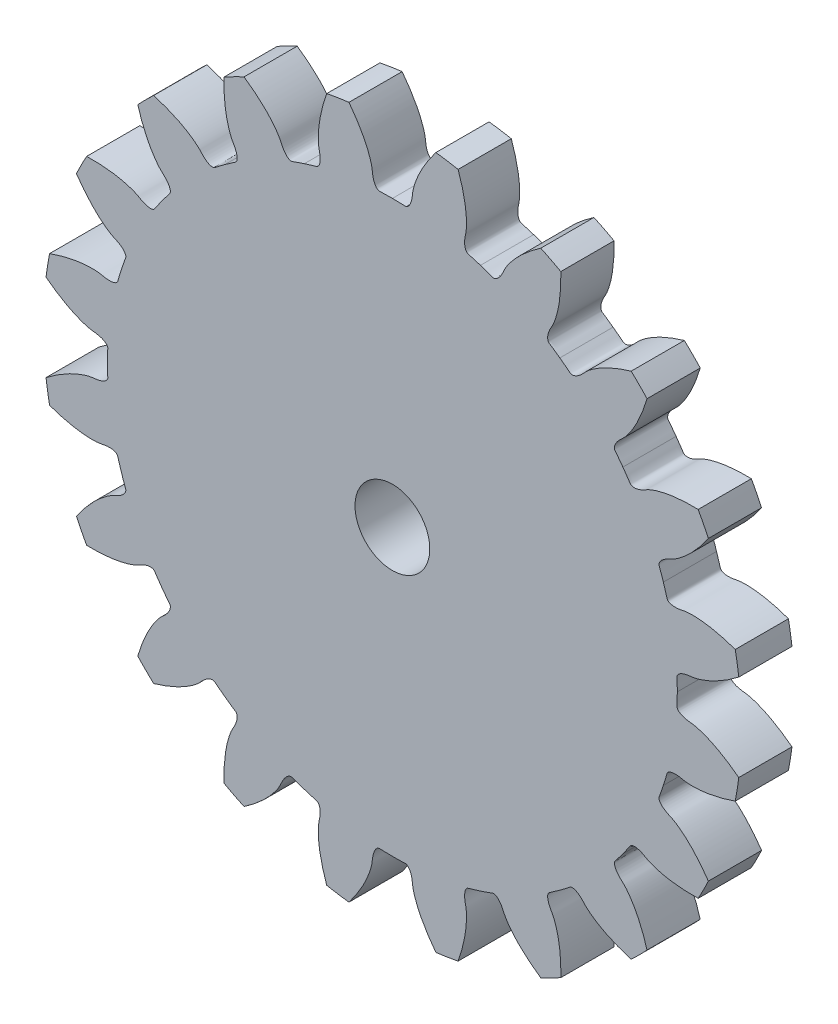
SolidWorks part; units mm, degrees
ref_plane "Front Plane" through (0, 0, 0) normal (0, 0, 1) x (1, 0, 0)
ref_plane "Top Plane" through (0, 0, 0) normal (0, 1, 0) x (1, 0, 0)
ref_plane "Right Plane" through (0, 0, 0) normal (1, 0, 0) x (0, 0, -1)
sketch "Model" plane through (0, 0, 0) normal (0, 0, 1) x (1, 0, 0)
  line L0 (-1.9599, -122.157) -> (1.9099, -120.8335)
  line L1 (1.9099, -120.8335) -> (1.9099, -119.1665)
  line L2 (1.9099, -119.1665) -> (-1.9599, -117.843)
  line L3 (-1.9599, -117.843) -> (-1.9599, -116.157)
  line L4 (-1.9599, -116.157) -> (1.9099, -114.8335)
  line L5 (1.9099, -114.8335) -> (1.9099, -113.1665)
  line L6 (1.9099, -113.1665) -> (-1.9599, -111.843)
  line L7 (-1.9599, -111.843) -> (-1.9599, -110.157)
  line L8 (-1.9599, -110.157) -> (1.9099, -108.8335)
  line L9 (1.9099, -108.8335) -> (1.9099, -107.1665)
  line L10 (1.9099, -107.1665) -> (-1.9599, -105.843)
  line L11 (-1.9599, -105.843) -> (-1.9599, -104.157)
  line L12 (-1.9599, -104.157) -> (1.9099, -102.8335)
  line L13 (1.9099, -102.8335) -> (1.9099, -101.1665)
  line L14 (1.9099, -101.1665) -> (-1.9599, -99.843)
  line L15 (-1.9599, -99.843) -> (-1.9599, -98.157)
  line L16 (-1.9599, -98.157) -> (1.9099, -96.8335)
  line L17 (1.9099, -96.8335) -> (1.9099, -95.1665)
  line L18 (1.9099, -95.1665) -> (-1.9599, -93.843)
  line L19 (-1.9599, -93.843) -> (-1.9599, -92.157)
  line L20 (-1.9599, -92.157) -> (1.9099, -90.8335)
  line L21 (1.9099, -90.8335) -> (1.9099, -89.1665)
  line L22 (1.9099, -89.1665) -> (-1.9599, -87.843)
  line L23 (-1.9599, -87.843) -> (-1.9599, -86.157)
  line L24 (-1.9599, -86.157) -> (1.9099, -84.8335)
  line L25 (1.9099, -84.8335) -> (1.9099, -83.1665)
  line L26 (1.9099, -83.1665) -> (-1.9599, -81.843)
  line L27 (-1.9599, -81.843) -> (-1.9599, -80.157)
  line L28 (-1.9599, -80.157) -> (1.9099, -78.8335)
  line L29 (1.9099, -78.8335) -> (1.9099, -77.1665)
  line L30 (1.9099, -77.1665) -> (-1.9599, -75.843)
  line L31 (-1.9599, -75.843) -> (-1.9599, -74.157)
  line L32 (-1.9599, -74.157) -> (1.9099, -72.8335)
  line L33 (1.9099, -72.8335) -> (1.9099, -71.1665)
  line L34 (1.9099, -71.1665) -> (-1.9599, -69.843)
  line L35 (-1.9599, -69.843) -> (-1.9599, -68.157)
  line L36 (-1.9599, -68.157) -> (1.9099, -66.8335)
  line L37 (1.9099, -66.8335) -> (1.9099, -65.1665)
  line L38 (1.9099, -65.1665) -> (-1.9599, -63.843)
  line L39 (-1.9599, -63.843) -> (-1.9599, -62.157)
  line L40 (-1.9599, -62.157) -> (1.9099, -60.8335)
  line L41 (1.9099, -60.8335) -> (1.9099, -59.1665)
  line L42 (1.9099, -59.1665) -> (-1.9599, -57.843)
  line L43 (-1.9599, -57.843) -> (-1.9599, -56.157)
  line L44 (-1.9599, -56.157) -> (1.9099, -54.8335)
  line L45 (1.9099, -54.8335) -> (1.9099, -53.1665)
  line L46 (1.9099, -53.1665) -> (-1.9599, -51.843)
  line L47 (-1.9599, -51.843) -> (-1.9599, -50.157)
  line L48 (-1.9599, -50.157) -> (1.9099, -48.8335)
  line L49 (1.9099, -48.8335) -> (1.9099, -47.1665)
  line L50 (1.9099, -47.1665) -> (-1.9599, -45.843)
  line L51 (-1.9599, -45.843) -> (-1.9599, -44.157)
  line L52 (-1.9599, -44.157) -> (1.9099, -42.8335)
  line L53 (1.9099, -42.8335) -> (1.9099, -41.1665)
  line L54 (1.9099, -41.1665) -> (-1.9599, -39.843)
  line L55 (-1.9599, -39.843) -> (-1.9599, -38.157)
  line L56 (-1.9599, -38.157) -> (1.9099, -36.8335)
  line L57 (1.9099, -36.8335) -> (1.9099, -35.1665)
  line L58 (1.9099, -35.1665) -> (-1.9599, -33.843)
  line L59 (-1.9599, -33.843) -> (-1.9599, -32.157)
  line L60 (-1.9599, -32.157) -> (1.9099, -30.8335)
  line L61 (1.9099, -30.8335) -> (1.9099, -29.1665)
  line L62 (1.9099, -29.1665) -> (-1.9599, -27.843)
  line L63 (-1.9599, -27.843) -> (-1.9599, -26.157)
  line L64 (-1.9599, -26.157) -> (1.9099, -24.8335)
  line L65 (1.9099, -24.8335) -> (1.9099, -23.1665)
  line L66 (1.9099, -23.1665) -> (-1.9599, -21.843)
  line L67 (-1.9599, -21.843) -> (-1.9599, -20.157)
  line L68 (-1.9599, -20.157) -> (1.9099, -18.8335)
  line L69 (1.9099, -18.8335) -> (1.9099, -17.1665)
  line L70 (1.9099, -17.1665) -> (-1.9599, -15.843)
  line L71 (-1.9599, -15.843) -> (-1.9599, -14.157)
  line L72 (-1.9599, -14.157) -> (1.9099, -12.8335)
  line L73 (1.9099, -12.8335) -> (1.9099, -11.1665)
  line L74 (1.9099, -11.1665) -> (-1.9599, -9.843)
  line L75 (-1.9599, -9.843) -> (-1.9599, -8.157)
  line L76 (-1.9599, -8.157) -> (1.9099, -6.8335)
  line L77 (1.9099, -6.8335) -> (1.9099, -5.1665)
  line L78 (1.9099, -5.1665) -> (-1.9599, -3.843)
  line L79 (-1.9599, -3.843) -> (-1.9599, -2.157)
  line L80 (-1.9599, -2.157) -> (1.9099, -0.8335)
  line L81 (1.9099, -0.8335) -> (1.9099, 0.8335)
  line L82 (1.9099, 0.8335) -> (-1.9599, 2.157)
  line L83 (-1.9599, 2.157) -> (-1.9599, 3.843)
  line L84 (-1.9599, 3.843) -> (1.9099, 5.1665)
  line L85 (1.9099, 5.1665) -> (1.9099, 6.8335)
  line L86 (1.9099, 6.8335) -> (-1.9599, 8.157)
  line L87 (-1.9599, 8.157) -> (-1.9599, 9.843)
  line L88 (-1.9599, 9.843) -> (1.9099, 11.1665)
  line L89 (1.9099, 11.1665) -> (1.9099, 12.8335)
  line L90 (1.9099, 12.8335) -> (-1.9599, 14.157)
  line L91 (-1.9599, 14.157) -> (-1.9599, 15.843)
  line L92 (-1.9599, 15.843) -> (1.9099, 17.1665)
  line L93 (1.9099, 17.1665) -> (1.9099, 18.8335)
  line L94 (1.9099, 18.8335) -> (-1.9599, 20.157)
  line L95 (-1.9599, 20.157) -> (-1.9599, 21.843)
  line L96 (-1.9599, 21.843) -> (1.9099, 23.1665)
  line L97 (1.9099, 23.1665) -> (1.9099, 24.8335)
  line L98 (1.9099, 24.8335) -> (-1.9599, 26.157)
  line L99 (-1.9599, 26.157) -> (-1.9599, 27.843)
  line L100 (-1.9599, 27.843) -> (1.9099, 29.1665)
  line L101 (1.9099, 29.1665) -> (1.9099, 30.8335)
  line L102 (1.9099, 30.8335) -> (-1.9599, 32.157)
  line L103 (-1.9599, 32.157) -> (-1.9599, 33.843)
  line L104 (-1.9599, 33.843) -> (1.9099, 35.1665)
  line L105 (1.9099, 35.1665) -> (1.9099, 36.8335)
  line L106 (1.9099, 36.8335) -> (-1.9599, 38.157)
  line L107 (-1.9599, 38.157) -> (-1.9599, 39.843)
  line L108 (-1.9599, 39.843) -> (1.9099, 41.1665)
  line L109 (1.9099, 41.1665) -> (1.9099, 42.8335)
  line L110 (1.9099, 42.8335) -> (-1.9599, 44.157)
  line L111 (-1.9599, 44.157) -> (-1.9599, 45.843)
  line L112 (-1.9599, 45.843) -> (1.9099, 47.1665)
  line L113 (1.9099, 47.1665) -> (1.9099, 48.8335)
  line L114 (1.9099, 48.8335) -> (-1.9599, 50.157)
  line L115 (-1.9599, 50.157) -> (-1.9599, 51.843)
  line L116 (-1.9599, 51.843) -> (1.9099, 53.1665)
  line L117 (1.9099, 53.1665) -> (1.9099, 54.8335)
  line L118 (1.9099, 54.8335) -> (-1.9599, 56.157)
  line L119 (-1.9599, 56.157) -> (-1.9599, 57.843)
  line L120 (-1.9599, 57.843) -> (1.9099, 59.1665)
  line L121 (1.9099, 59.1665) -> (1.9099, 60.8335)
  line L122 (1.9099, 60.8335) -> (-1.9599, 62.157)
  line L123 (-1.9599, 62.157) -> (-1.9599, 63.843)
  line L124 (-1.9599, 63.843) -> (1.9099, 65.1665)
  line L125 (1.9099, 65.1665) -> (1.9099, 66.8335)
  line L126 (1.9099, 66.8335) -> (-1.9599, 68.157)
  line L127 (-1.9599, 68.157) -> (-1.9599, 69.843)
  line L128 (-1.9599, 69.843) -> (1.9099, 71.1665)
  line L129 (1.9099, 71.1665) -> (1.9099, 72.8335)
  line L130 (1.9099, 72.8335) -> (-1.9599, 74.157)
  line L131 (-1.9599, 74.157) -> (-1.9599, 75.843)
  line L132 (-1.9599, 75.843) -> (1.9099, 77.1665)
  line L133 (1.9099, 77.1665) -> (1.9099, 78.8335)
  line L134 (1.9099, 78.8335) -> (-1.9599, 80.157)
  line L135 (-1.9599, 80.157) -> (-1.9599, 81.843)
  line L136 (-1.9599, 81.843) -> (1.9099, 83.1665)
  line L137 (1.9099, 83.1665) -> (1.9099, 84.8335)
  line L138 (1.9099, 84.8335) -> (-1.9599, 86.157)
  line L139 (-1.9599, 86.157) -> (-1.9599, 87.843)
  line L140 (-1.9599, 87.843) -> (1.9099, 89.1665)
  line L141 (1.9099, 89.1665) -> (1.9099, 90.8335)
  line L142 (1.9099, 90.8335) -> (-1.9599, 92.157)
  line L143 (-1.9599, 92.157) -> (-1.9599, 93.843)
  line L144 (-1.9599, 93.843) -> (1.9099, 95.1665)
  line L145 (1.9099, 95.1665) -> (1.9099, 96.8335)
  line L146 (1.9099, 96.8335) -> (-1.9599, 98.157)
  line L147 (-1.9599, 98.157) -> (-1.9599, 99.843)
  line L148 (-1.9599, 99.843) -> (1.9099, 101.1665)
  line L149 (1.9099, 101.1665) -> (1.9099, 102.8335)
  line L150 (1.9099, 102.8335) -> (-1.9599, 104.157)
  line L151 (-1.9599, 104.157) -> (-1.9599, 105.843)
  line L152 (-1.9599, 105.843) -> (1.9099, 107.1665)
  line L153 (1.9099, 107.1665) -> (1.9099, 108.8335)
  line L154 (1.9099, 108.8335) -> (-1.9599, 110.157)
  line L155 (-1.9599, 110.157) -> (-1.9599, 111.843)
  line L156 (-1.9599, 111.843) -> (1.9099, 113.1665)
  line L157 (1.9099, 113.1665) -> (1.9099, 114.8335)
  line L158 (1.9099, 114.8335) -> (-1.9599, 116.157)
  line L159 (-1.9599, 116.157) -> (-1.9599, 117.843)
  line L160 (-1.9599, 117.843) -> (1.9099, 119.1665)
  line L161 (1.9099, 119.1665) -> (1.9099, 120.8335)
  line L162 (1.9099, 120.8335) -> (-1.9599, 122.157)
  line L163 (-1.9599, 122.157) -> (-1.9599, 123)
  line L164 (-1.9599, 123) -> (-9.5993, 123)
  line L165 (-9.5993, 123) -> (-9.5993, -123)
  line L166 (-9.5993, -123) -> (-1.9599, -123)
  line L167 (-1.9599, -123) -> (-1.9599, -122.157)
  line L168 (-1.5377, 3.9366) -> (-1.6512, 3.2864)
  line L169 (-1.6512, 3.2864) -> (-1.7442, 2.6331)
  line L170 (-1.7442, 2.6331) -> (-1.7455, 2.6215)
  line L171 (-1.7455, 2.6215) -> (-1.7388, 2.6161)
  line L172 (-1.7388, 2.6161) -> (-1.4771, 2.4198)
  line L173 (-1.4771, 2.4198) -> (-1.2239, 2.242)
  line L174 (-1.2239, 2.242) -> (-0.9803, 2.082)
  line L175 (-0.9803, 2.082) -> (-0.7469, 1.9391)
  line L176 (-0.7469, 1.9391) -> (-0.5246, 1.8124)
  line L177 (-0.5246, 1.8124) -> (-0.3143, 1.7011)
  line L178 (-0.3143, 1.7011) -> (-0.1165, 1.6044)
  line L179 (-0.1165, 1.6044) -> (0.0679, 1.5212)
  line L180 (0.0679, 1.5212) -> (0.2383, 1.4506)
  line L181 (0.2383, 1.4506) -> (0.3942, 1.3918)
  line L182 (0.3942, 1.3918) -> (0.535, 1.3436)
  line L183 (0.535, 1.3436) -> (0.6602, 1.3051)
  line L184 (0.6602, 1.3051) -> (0.7694, 1.2753)
  line L185 (0.7694, 1.2753) -> (0.862, 1.2531)
  line L186 (0.862, 1.2531) -> (0.9379, 1.2374)
  line L187 (0.9379, 1.2374) -> (0.9966, 1.2272)
  line L188 (0.9966, 1.2272) -> (1.038, 1.2213)
  line L189 (1.038, 1.2213) -> (1.0618, 1.2187)
  line L190 (1.0618, 1.2187) -> (1.0916, 1.2164)
  line L191 (1.0916, 1.2164) -> (1.2696, 1.1958)
  line L192 (1.2696, 1.1958) -> (1.4284, 1.1659)
  line L193 (1.4284, 1.1659) -> (1.5676, 1.1277)
  line L194 (1.5676, 1.1277) -> (1.6869, 1.0826)
  line L195 (1.6869, 1.0826) -> (1.7859, 1.0316)
  line L196 (1.7859, 1.0316) -> (1.8646, 0.9761)
  line L197 (1.8646, 0.9761) -> (1.9226, 0.9172)
  line L198 (1.9226, 0.9172) -> (1.9599, 0.8563)
  line L199 (1.9599, 0.8563) -> (1.9764, 0.7945)
  line L200 (1.9764, 0.7945) -> (1.9599, 0.2692)
  line L201 (1.9599, 0.2692) -> (1.9599, -0.2692)
  line L202 (1.9599, -0.2692) -> (1.9764, -0.7945)
  line L203 (1.9764, -0.7945) -> (1.9599, -0.8563)
  line L204 (1.9599, -0.8563) -> (1.9226, -0.9172)
  line L205 (1.9226, -0.9172) -> (1.8646, -0.9761)
  line L206 (1.8646, -0.9761) -> (1.7859, -1.0316)
  line L207 (1.7859, -1.0316) -> (1.6869, -1.0826)
  line L208 (1.6869, -1.0826) -> (1.5676, -1.1277)
  line L209 (1.5676, -1.1277) -> (1.4284, -1.1659)
  line L210 (1.4284, -1.1659) -> (1.2696, -1.1958)
  line L211 (1.2696, -1.1958) -> (1.0916, -1.2164)
  line L212 (1.0916, -1.2164) -> (1.0618, -1.2187)
  line L213 (1.0618, -1.2187) -> (1.038, -1.2213)
  line L214 (1.038, -1.2213) -> (0.9966, -1.2272)
  line L215 (0.9966, -1.2272) -> (0.9379, -1.2374)
  line L216 (0.9379, -1.2374) -> (0.862, -1.2531)
  line L217 (0.862, -1.2531) -> (0.7694, -1.2753)
  line L218 (0.7694, -1.2753) -> (0.6602, -1.3051)
  line L219 (0.6602, -1.3051) -> (0.535, -1.3436)
  line L220 (0.535, -1.3436) -> (0.3942, -1.3918)
  line L221 (0.3942, -1.3918) -> (0.2383, -1.4506)
  line L222 (0.2383, -1.4506) -> (0.0679, -1.5212)
  line L223 (0.0679, -1.5212) -> (-0.1165, -1.6044)
  line L224 (-0.1165, -1.6044) -> (-0.3143, -1.7011)
  line L225 (-0.3143, -1.7011) -> (-0.5246, -1.8124)
  line L226 (-0.5246, -1.8124) -> (-0.7469, -1.9391)
  line L227 (-0.7469, -1.9391) -> (-0.9803, -2.082)
  line L228 (-0.9803, -2.082) -> (-1.2239, -2.242)
  line L229 (-1.2239, -2.242) -> (-1.4771, -2.4198)
  line L230 (-1.4771, -2.4198) -> (-1.7388, -2.6161)
  line L231 (-1.7388, -2.6161) -> (-1.7455, -2.6215)
  line L232 (-1.7455, -2.6215) -> (-1.7442, -2.6331)
  line L233 (-1.7442, -2.6331) -> (-1.6512, -3.2864)
  line L234 (-1.6512, -3.2864) -> (-1.5377, -3.9366)
  line L235 (-1.5377, -3.9366) -> (-1.5354, -3.948)
  line L236 (-1.5354, -3.948) -> (-1.5274, -3.951)
  line L237 (-1.5274, -3.951) -> (-1.2178, -4.0569)
  line L238 (-1.2178, -4.0569) -> (-0.9221, -4.1477)
  line L239 (-0.9221, -4.1477) -> (-0.6409, -4.2246)
  line L240 (-0.6409, -4.2246) -> (-0.3748, -4.2884)
  line L241 (-0.3748, -4.2884) -> (-0.1243, -4.3402)
  line L242 (-0.1243, -4.3402) -> (0.1102, -4.381)
  line L243 (0.1102, -4.381) -> (0.3281, -4.412)
  line L244 (0.3281, -4.412) -> (0.5292, -4.4341)
  line L245 (0.5292, -4.4341) -> (0.7132, -4.4485)
  line L246 (0.7132, -4.4485) -> (0.8796, -4.4563)
  line L247 (0.8796, -4.4563) -> (1.0284, -4.4586)
  line L248 (1.0284, -4.4586) -> (1.1593, -4.4565)
  line L249 (1.1593, -4.4565) -> (1.2724, -4.4511)
  line L250 (1.2724, -4.4511) -> (1.3673, -4.4436)
  line L251 (1.3673, -4.4436) -> (1.4443, -4.4351)
  line L252 (1.4443, -4.4351) -> (1.5034, -4.4267)
  line L253 (1.5034, -4.4267) -> (1.5445, -4.4195)
  line L254 (1.5445, -4.4195) -> (1.568, -4.4146)
  line L255 (1.568, -4.4146) -> (1.5971, -4.4076)
  line L256 (1.5971, -4.4076) -> (1.7727, -4.3722)
  line L257 (1.7727, -4.3722) -> (1.933, -4.3516)
  line L258 (1.933, -4.3516) -> (2.0771, -4.3448)
  line L259 (2.0771, -4.3448) -> (2.2045, -4.3509)
  line L260 (2.2045, -4.3509) -> (2.3145, -4.3688)
  line L261 (2.3145, -4.3688) -> (2.4064, -4.3973)
  line L262 (2.4064, -4.3973) -> (2.4798, -4.4353)
  line L263 (2.4798, -4.4353) -> (2.5341, -4.4818)
  line L264 (2.5341, -4.4818) -> (2.5689, -4.5354)
  line L265 (2.5689, -4.5354) -> (2.7155, -5.0401)
  line L266 (2.7155, -5.0401) -> (2.8819, -5.5522)
  line L267 (2.8819, -5.5522) -> (3.0599, -6.0467)
  line L268 (3.0599, -6.0467) -> (3.0633, -6.1105)
  line L269 (3.0633, -6.1105) -> (3.0467, -6.18)
  line L270 (3.0467, -6.18) -> (3.0097, -6.2539)
  line L271 (3.0097, -6.2539) -> (2.9521, -6.331)
  line L272 (2.9521, -6.331) -> (2.8736, -6.4101)
  line L273 (2.8736, -6.4101) -> (2.7741, -6.4899)
  line L274 (2.7741, -6.4899) -> (2.6535, -6.5692)
  line L275 (2.6535, -6.5692) -> (2.5118, -6.6468)
  line L276 (2.5118, -6.6468) -> (2.3488, -6.7213)
  line L277 (2.3488, -6.7213) -> (2.3212, -6.7327)
  line L278 (2.3212, -6.7327) -> (2.2993, -6.7426)
  line L279 (2.2993, -6.7426) -> (2.2618, -6.761)
  line L280 (2.2618, -6.761) -> (2.2091, -6.7888)
  line L281 (2.2091, -6.7888) -> (2.1418, -6.8272)
  line L282 (2.1418, -6.8272) -> (2.0605, -6.877)
  line L283 (2.0605, -6.877) -> (1.966, -6.939)
  line L284 (1.966, -6.939) -> (1.8588, -7.0143)
  line L285 (1.8588, -7.0143) -> (1.7398, -7.1036)
  line L286 (1.7398, -7.1036) -> (1.6097, -7.2078)
  line L287 (1.6097, -7.2078) -> (1.4694, -7.3275)
  line L288 (1.4694, -7.3275) -> (1.3197, -7.4636)
  line L289 (1.3197, -7.4636) -> (1.1616, -7.6168)
  line L290 (1.1616, -7.6168) -> (0.9959, -7.7876)
  line L291 (0.9959, -7.7876) -> (0.8236, -7.9768)
  line L292 (0.8236, -7.9768) -> (0.6459, -8.1848)
  line L293 (0.6459, -8.1848) -> (0.4635, -8.4123)
  line L294 (0.4635, -8.4123) -> (0.2777, -8.6596)
  line L295 (0.2777, -8.6596) -> (0.0895, -8.9272)
  line L296 (0.0895, -8.9272) -> (0.0848, -8.9344)
  line L297 (0.0848, -8.9344) -> (0.0896, -8.945)
  line L298 (0.0896, -8.945) -> (0.3799, -9.5376)
  line L299 (0.3799, -9.5376) -> (0.6887, -10.1209)
  line L300 (0.6887, -10.1209) -> (0.6945, -10.131)
  line L301 (0.6945, -10.131) -> (0.7031, -10.1314)
  line L302 (0.7031, -10.1314) -> (1.0302, -10.1364)
  line L303 (1.0302, -10.1364) -> (1.3395, -10.1315)
  line L304 (1.3395, -10.1315) -> (1.6307, -10.1177)
  line L305 (1.6307, -10.1177) -> (1.9035, -10.0961)
  line L306 (1.9035, -10.0961) -> (2.1578, -10.0679)
  line L307 (2.1578, -10.0679) -> (2.3934, -10.0343)
  line L308 (2.3934, -10.0343) -> (2.6102, -9.9964)
  line L309 (2.6102, -9.9964) -> (2.8083, -9.9553)
  line L310 (2.8083, -9.9553) -> (2.9877, -9.9122)
  line L311 (2.9877, -9.9122) -> (3.1484, -9.8682)
  line L312 (3.1484, -9.8682) -> (3.2906, -9.8244)
  line L313 (3.2906, -9.8244) -> (3.4145, -9.7819)
  line L314 (3.4145, -9.7819) -> (3.5203, -9.7419)
  line L315 (3.5203, -9.7419) -> (3.6083, -9.7054)
  line L316 (3.6083, -9.7054) -> (3.6789, -9.6735)
  line L317 (3.6789, -9.6735) -> (3.7324, -9.6473)
  line L318 (3.7324, -9.6473) -> (3.7694, -9.6277)
  line L319 (3.7694, -9.6277) -> (3.7902, -9.6158)
  line L320 (3.7902, -9.6158) -> (3.8157, -9.6002)
  line L321 (3.8157, -9.6002) -> (3.9718, -9.5122)
  line L322 (3.9718, -9.5122) -> (4.1178, -9.4431)
  line L323 (4.1178, -9.4431) -> (4.2529, -9.3921)
  line L324 (4.2529, -9.3921) -> (4.3759, -9.3585)
  line L325 (4.3759, -9.3585) -> (4.486, -9.3415)
  line L326 (4.486, -9.3415) -> (4.5822, -9.3402)
  line L327 (4.5822, -9.3402) -> (4.6638, -9.3538)
  line L328 (4.6638, -9.3538) -> (4.7297, -9.3811)
  line L329 (4.7297, -9.3811) -> (4.7794, -9.4214)
  line L330 (4.7794, -9.4214) -> (5.0748, -9.8561)
  line L331 (5.0748, -9.8561) -> (5.3913, -10.2917)
  line L332 (5.3913, -10.2917) -> (5.7134, -10.707)
  line L333 (5.7134, -10.707) -> (5.7364, -10.7667)
  line L334 (5.7364, -10.7667) -> (5.742, -10.8379)
  line L335 (5.742, -10.8379) -> (5.7297, -10.9196)
  line L336 (5.7297, -10.9196) -> (5.6987, -11.0107)
  line L337 (5.6987, -11.0107) -> (5.6485, -11.1102)
  line L338 (5.6485, -11.1102) -> (5.5786, -11.2168)
  line L339 (5.5786, -11.2168) -> (5.4884, -11.3295)
  line L340 (5.4884, -11.3295) -> (5.3775, -11.447)
  line L341 (5.3775, -11.447) -> (5.2456, -11.5683)
  line L342 (5.2456, -11.5683) -> (5.2228, -11.5877)
  line L343 (5.2228, -11.5877) -> (5.2051, -11.6038)
  line L344 (5.2051, -11.6038) -> (5.1751, -11.6329)
  line L345 (5.1751, -11.6329) -> (5.1336, -11.6757)
  line L346 (5.1336, -11.6757) -> (5.0815, -11.733)
  line L347 (5.0815, -11.733) -> (5.0195, -11.8054)
  line L348 (5.0195, -11.8054) -> (4.9488, -11.8937)
  line L349 (4.9488, -11.8937) -> (4.8701, -11.9984)
  line L350 (4.8701, -11.9984) -> (4.7845, -12.1201)
  line L351 (4.7845, -12.1201) -> (4.693, -12.2594)
  line L352 (4.693, -12.2594) -> (4.5965, -12.4166)
  line L353 (4.5965, -12.4166) -> (4.4962, -12.5923)
  line L354 (4.4962, -12.5923) -> (4.3932, -12.7868)
  line L355 (4.3932, -12.7868) -> (4.2884, -13.0005)
  line L356 (4.2884, -13.0005) -> (4.1831, -13.2337)
  line L357 (4.1831, -13.2337) -> (4.0782, -13.4865)
  line L358 (4.0782, -13.4865) -> (3.9751, -13.7591)
  line L359 (3.9751, -13.7591) -> (3.8748, -14.0517)
  line L360 (3.8748, -14.0517) -> (3.7785, -14.3644)
  line L361 (3.7785, -14.3644) -> (3.7763, -14.3727)
  line L362 (3.7763, -14.3727) -> (3.7841, -14.3813)
  line L363 (3.7841, -14.3813) -> (4.2434, -14.8552)
  line L364 (4.2434, -14.8552) -> (4.7173, -15.3145)
  line L365 (4.7173, -15.3145) -> (4.7259, -15.3223)
  line L366 (4.7259, -15.3223) -> (4.7342, -15.3201)
  line L367 (4.7342, -15.3201) -> (5.0469, -15.2238)
  line L368 (5.0469, -15.2238) -> (5.3395, -15.1235)
  line L369 (5.3395, -15.1235) -> (5.6121, -15.0203)
  line L370 (5.6121, -15.0203) -> (5.8649, -14.9155)
  line L371 (5.8649, -14.9155) -> (6.0981, -14.8102)
  line L372 (6.0981, -14.8102) -> (6.3117, -14.7054)
  line L373 (6.3117, -14.7054) -> (6.5063, -14.6023)
  line L374 (6.5063, -14.6023) -> (6.682, -14.5021)
  line L375 (6.682, -14.5021) -> (6.8392, -14.4056)
  line L376 (6.8392, -14.4056) -> (6.9785, -14.3141)
  line L377 (6.9785, -14.3141) -> (7.1002, -14.2285)
  line L378 (7.1002, -14.2285) -> (7.2049, -14.1498)
  line L379 (7.2049, -14.1498) -> (7.2932, -14.0791)
  line L380 (7.2932, -14.0791) -> (7.3656, -14.0171)
  line L381 (7.3656, -14.0171) -> (7.4229, -13.965)
  line L382 (7.4229, -13.965) -> (7.4657, -13.9235)
  line L383 (7.4657, -13.9235) -> (7.4948, -13.8935)
  line L384 (7.4948, -13.8935) -> (7.5109, -13.8758)
  line L385 (7.5109, -13.8758) -> (7.5303, -13.853)
  line L386 (7.5303, -13.853) -> (7.6515, -13.7211)
  line L387 (7.6515, -13.7211) -> (7.7691, -13.6102)
  line L388 (7.7691, -13.6102) -> (7.8818, -13.52)
  line L389 (7.8818, -13.52) -> (7.9884, -13.4501)
  line L390 (7.9884, -13.4501) -> (8.0879, -13.3999)
  line L391 (8.0879, -13.3999) -> (8.179, -13.3689)
  line L392 (8.179, -13.3689) -> (8.2607, -13.3566)
  line L393 (8.2607, -13.3566) -> (8.3319, -13.3622)
  line L394 (8.3319, -13.3622) -> (8.3916, -13.3852)
  line L395 (8.3916, -13.3852) -> (8.8069, -13.7073)
  line L396 (8.8069, -13.7073) -> (9.2425, -14.0238)
  line L397 (9.2425, -14.0238) -> (9.6772, -14.3192)
  line L398 (9.6772, -14.3192) -> (9.7175, -14.3688)
  line L399 (9.7175, -14.3688) -> (9.7448, -14.4348)
  line L400 (9.7448, -14.4348) -> (9.7584, -14.5164)
  line L401 (9.7584, -14.5164) -> (9.7571, -14.6126)
  line L402 (9.7571, -14.6126) -> (9.7401, -14.7227)
  line L403 (9.7401, -14.7227) -> (9.7065, -14.8457)
  line L404 (9.7065, -14.8457) -> (9.6555, -14.9808)
  line L405 (9.6555, -14.9808) -> (9.5864, -15.1268)
  line L406 (9.5864, -15.1268) -> (9.4984, -15.2829)
  line L407 (9.4984, -15.2829) -> (9.4828, -15.3084)
  line L408 (9.4828, -15.3084) -> (9.4709, -15.3292)
  line L409 (9.4709, -15.3292) -> (9.4513, -15.3661)
  line L410 (9.4513, -15.3661) -> (9.4251, -15.4197)
  line L411 (9.4251, -15.4197) -> (9.3932, -15.4903)
  line L412 (9.3932, -15.4903) -> (9.3567, -15.5783)
  line L413 (9.3567, -15.5783) -> (9.3167, -15.6841)
  line L414 (9.3167, -15.6841) -> (9.2742, -15.808)
  line L415 (9.2742, -15.808) -> (9.2304, -15.9502)
  line L416 (9.2304, -15.9502) -> (9.1864, -16.1109)
  line L417 (9.1864, -16.1109) -> (9.1433, -16.2903)
  line L418 (9.1433, -16.2903) -> (9.1022, -16.4884)
  line L419 (9.1022, -16.4884) -> (9.0643, -16.7052)
  line L420 (9.0643, -16.7052) -> (9.0307, -16.9408)
  line L421 (9.0307, -16.9408) -> (9.0025, -17.1951)
  line L422 (9.0025, -17.1951) -> (8.9809, -17.4679)
  line L423 (8.9809, -17.4679) -> (8.9671, -17.7591)
  line L424 (8.9671, -17.7591) -> (8.9622, -18.0684)
  line L425 (8.9622, -18.0684) -> (8.9672, -18.3955)
  line L426 (8.9672, -18.3955) -> (8.9676, -18.4041)
  line L427 (8.9676, -18.4041) -> (8.9777, -18.4098)
  line L428 (8.9777, -18.4098) -> (9.561, -18.7187)
  line L429 (9.561, -18.7187) -> (10.1536, -19.009)
  line L430 (10.1536, -19.009) -> (10.1642, -19.0138)
  line L431 (10.1642, -19.0138) -> (10.1714, -19.0091)
  line L432 (10.1714, -19.0091) -> (10.439, -18.8209)
  line L433 (10.439, -18.8209) -> (10.6863, -18.6351)
  line L434 (10.6863, -18.6351) -> (10.9138, -18.4527)
  line L435 (10.9138, -18.4527) -> (11.1218, -18.2749)
  line L436 (11.1218, -18.2749) -> (11.311, -18.1027)
  line L437 (11.311, -18.1027) -> (11.4818, -17.937)
  line L438 (11.4818, -17.937) -> (11.635, -17.7789)
  line L439 (11.635, -17.7789) -> (11.7711, -17.6292)
  line L440 (11.7711, -17.6292) -> (11.8908, -17.4889)
  line L441 (11.8908, -17.4889) -> (11.995, -17.3588)
  line L442 (11.995, -17.3588) -> (12.0843, -17.2398)
  line L443 (12.0843, -17.2398) -> (12.1596, -17.1326)
  line L444 (12.1596, -17.1326) -> (12.2216, -17.038)
  line L445 (12.2216, -17.038) -> (12.2714, -16.9568)
  line L446 (12.2714, -16.9568) -> (12.3098, -16.8895)
  line L447 (12.3098, -16.8895) -> (12.3376, -16.8368)
  line L448 (12.3376, -16.8368) -> (12.356, -16.7993)
  line L449 (12.356, -16.7993) -> (12.3659, -16.7774)
  line L450 (12.3659, -16.7774) -> (12.3773, -16.7498)
  line L451 (12.3773, -16.7498) -> (12.4518, -16.5868)
  line L452 (12.4518, -16.5868) -> (12.5294, -16.4451)
  line L453 (12.5294, -16.4451) -> (12.6087, -16.3245)
  line L454 (12.6087, -16.3245) -> (12.6885, -16.225)
  line L455 (12.6885, -16.225) -> (12.7676, -16.1465)
  line L456 (12.7676, -16.1465) -> (12.8447, -16.0889)
  line L457 (12.8447, -16.0889) -> (12.9186, -16.0519)
  line L458 (12.9186, -16.0519) -> (12.9881, -16.0353)
  line L459 (12.9881, -16.0353) -> (13.0519, -16.0387)
  line L460 (13.0519, -16.0387) -> (13.5464, -16.2167)
  line L461 (13.5464, -16.2167) -> (14.0585, -16.3831)
  line L462 (14.0585, -16.3831) -> (14.5632, -16.5297)
  line L463 (14.5632, -16.5297) -> (14.6168, -16.5645)
  line L464 (14.6168, -16.5645) -> (14.6633, -16.6188)
  line L465 (14.6633, -16.6188) -> (14.7013, -16.6922)
  line L466 (14.7013, -16.6922) -> (14.7298, -16.7841)
  line L467 (14.7298, -16.7841) -> (14.7477, -16.8941)
  line L468 (14.7477, -16.8941) -> (14.7538, -17.0214)
  line L469 (14.7538, -17.0214) -> (14.747, -17.1656)
  line L470 (14.747, -17.1656) -> (14.7264, -17.3259)
  line L471 (14.7264, -17.3259) -> (14.691, -17.5015)
  line L472 (14.691, -17.5015) -> (14.684, -17.5306)
  line L473 (14.684, -17.5306) -> (14.6791, -17.5541)
  line L474 (14.6791, -17.5541) -> (14.6719, -17.5952)
  line L475 (14.6719, -17.5952) -> (14.6635, -17.6543)
  line L476 (14.6635, -17.6543) -> (14.655, -17.7312)
  line L477 (14.655, -17.7312) -> (14.6475, -17.8262)
  line L478 (14.6475, -17.8262) -> (14.6421, -17.9392)
  line L479 (14.6421, -17.9392) -> (14.64, -18.0702)
  line L480 (14.64, -18.0702) -> (14.6423, -18.219)
  line L481 (14.6423, -18.219) -> (14.6501, -18.3854)
  line L482 (14.6501, -18.3854) -> (14.6645, -18.5693)
  line L483 (14.6645, -18.5693) -> (14.6866, -18.7704)
  line L484 (14.6866, -18.7704) -> (14.7176, -18.9884)
  line L485 (14.7176, -18.9884) -> (14.7584, -19.2229)
  line L486 (14.7584, -19.2229) -> (14.8102, -19.4734)
  line L487 (14.8102, -19.4734) -> (14.874, -19.7395)
  line L488 (14.874, -19.7395) -> (14.9508, -20.0207)
  line L489 (14.9508, -20.0207) -> (15.0417, -20.3164)
  line L490 (15.0417, -20.3164) -> (15.1476, -20.6259)
  line L491 (15.1476, -20.6259) -> (15.1506, -20.634)
  line L492 (15.1506, -20.634) -> (15.162, -20.6363)
  line L493 (15.162, -20.6363) -> (15.8121, -20.7498)
  line L494 (15.8121, -20.7498) -> (16.4655, -20.8428)
  line L495 (16.4655, -20.8428) -> (16.4771, -20.8441)
  line L496 (16.4771, -20.8441) -> (16.4825, -20.8374)
  line L497 (16.4825, -20.8374) -> (16.6788, -20.5757)
  line L498 (16.6788, -20.5757) -> (16.8566, -20.3225)
  line L499 (16.8566, -20.3225) -> (17.0166, -20.0789)
  line L500 (17.0166, -20.0789) -> (17.1595, -19.8455)
  line L501 (17.1595, -19.8455) -> (17.2862, -19.6232)
  line L502 (17.2862, -19.6232) -> (17.3974, -19.4129)
  line L503 (17.3974, -19.4129) -> (17.4942, -19.2151)
  line L504 (17.4942, -19.2151) -> (17.5774, -19.0307)
  line L505 (17.5774, -19.0307) -> (17.648, -18.8603)
  line L506 (17.648, -18.8603) -> (17.7068, -18.7044)
  line L507 (17.7068, -18.7044) -> (17.755, -18.5636)
  line L508 (17.755, -18.5636) -> (17.7935, -18.4384)
  line L509 (17.7935, -18.4384) -> (17.8233, -18.3292)
  line L510 (17.8233, -18.3292) -> (17.8455, -18.2366)
  line L511 (17.8455, -18.2366) -> (17.8612, -18.1607)
  line L512 (17.8612, -18.1607) -> (17.8714, -18.102)
  line L513 (17.8714, -18.102) -> (17.8773, -18.0606)
  line L514 (17.8773, -18.0606) -> (17.8799, -18.0368)
  line L515 (17.8799, -18.0368) -> (17.8822, -18.007)
  line L516 (17.8822, -18.007) -> (17.9028, -17.829)
  line L517 (17.9028, -17.829) -> (17.9327, -17.6702)
  line L518 (17.9327, -17.6702) -> (17.9709, -17.531)
  line L519 (17.9709, -17.531) -> (18.016, -17.4117)
  line L520 (18.016, -17.4117) -> (18.067, -17.3127)
  line L521 (18.067, -17.3127) -> (18.1225, -17.234)
  line L522 (18.1225, -17.234) -> (18.1814, -17.176)
  line L523 (18.1814, -17.176) -> (18.2423, -17.1387)
  line L524 (18.2423, -17.1387) -> (18.3041, -17.1222)
  line L525 (18.3041, -17.1222) -> (18.8294, -17.1387)
  line L526 (18.8294, -17.1387) -> (19.3678, -17.1387)
  line L527 (19.3678, -17.1387) -> (19.8931, -17.1222)
  line L528 (19.8931, -17.1222) -> (19.9549, -17.1387)
  line L529 (19.9549, -17.1387) -> (20.0158, -17.176)
  line L530 (20.0158, -17.176) -> (20.0747, -17.234)
  line L531 (20.0747, -17.234) -> (20.1302, -17.3127)
  line L532 (20.1302, -17.3127) -> (20.1812, -17.4117)
  line L533 (20.1812, -17.4117) -> (20.2263, -17.531)
  line L534 (20.2263, -17.531) -> (20.2645, -17.6702)
  line L535 (20.2645, -17.6702) -> (20.2944, -17.829)
  line L536 (20.2944, -17.829) -> (20.315, -18.007)
  line L537 (20.315, -18.007) -> (20.3173, -18.0368)
  line L538 (20.3173, -18.0368) -> (20.3199, -18.0606)
  line L539 (20.3199, -18.0606) -> (20.3258, -18.102)
  line L540 (20.3258, -18.102) -> (20.336, -18.1607)
  line L541 (20.336, -18.1607) -> (20.3517, -18.2366)
  line L542 (20.3517, -18.2366) -> (20.3739, -18.3292)
  line L543 (20.3739, -18.3292) -> (20.4037, -18.4384)
  line L544 (20.4037, -18.4384) -> (20.4422, -18.5636)
  line L545 (20.4422, -18.5636) -> (20.4904, -18.7044)
  line L546 (20.4904, -18.7044) -> (20.5492, -18.8603)
  line L547 (20.5492, -18.8603) -> (20.6198, -19.0307)
  line L548 (20.6198, -19.0307) -> (20.703, -19.2151)
  line L549 (20.703, -19.2151) -> (20.7997, -19.4129)
  line L550 (20.7997, -19.4129) -> (20.911, -19.6232)
  line L551 (20.911, -19.6232) -> (21.0377, -19.8455)
  line L552 (21.0377, -19.8455) -> (21.1806, -20.0789)
  line L553 (21.1806, -20.0789) -> (21.3406, -20.3225)
  line L554 (21.3406, -20.3225) -> (21.5184, -20.5757)
  line L555 (21.5184, -20.5757) -> (21.7147, -20.8374)
  line L556 (21.7147, -20.8374) -> (21.7201, -20.8441)
  line L557 (21.7201, -20.8441) -> (21.7317, -20.8428)
  line L558 (21.7317, -20.8428) -> (22.385, -20.7498)
  line L559 (22.385, -20.7498) -> (23.0352, -20.6363)
  line L560 (23.0352, -20.6363) -> (23.0466, -20.634)
  line L561 (23.0466, -20.634) -> (23.0496, -20.6259)
  line L562 (23.0496, -20.6259) -> (23.1555, -20.3164)
  line L563 (23.1555, -20.3164) -> (23.2463, -20.0207)
  line L564 (23.2463, -20.0207) -> (23.3232, -19.7395)
  line L565 (23.3232, -19.7395) -> (23.387, -19.4734)
  line L566 (23.387, -19.4734) -> (23.4388, -19.2229)
  line L567 (23.4388, -19.2229) -> (23.4796, -18.9884)
  line L568 (23.4796, -18.9884) -> (23.5106, -18.7704)
  line L569 (23.5106, -18.7704) -> (23.5327, -18.5693)
  line L570 (23.5327, -18.5693) -> (23.5471, -18.3854)
  line L571 (23.5471, -18.3854) -> (23.5549, -18.219)
  line L572 (23.5549, -18.219) -> (23.5572, -18.0702)
  line L573 (23.5572, -18.0702) -> (23.5551, -17.9392)
  line L574 (23.5551, -17.9392) -> (23.5497, -17.8262)
  line L575 (23.5497, -17.8262) -> (23.5422, -17.7312)
  line L576 (23.5422, -17.7312) -> (23.5337, -17.6543)
  line L577 (23.5337, -17.6543) -> (23.5253, -17.5952)
  line L578 (23.5253, -17.5952) -> (23.5181, -17.5541)
  line L579 (23.5181, -17.5541) -> (23.5132, -17.5306)
  line L580 (23.5132, -17.5306) -> (23.5062, -17.5015)
  line L581 (23.5062, -17.5015) -> (23.4708, -17.3259)
  line L582 (23.4708, -17.3259) -> (23.4502, -17.1656)
  line L583 (23.4502, -17.1656) -> (23.4434, -17.0214)
  line L584 (23.4434, -17.0214) -> (23.4495, -16.8941)
  line L585 (23.4495, -16.8941) -> (23.4674, -16.7841)
  line L586 (23.4674, -16.7841) -> (23.4959, -16.6922)
  line L587 (23.4959, -16.6922) -> (23.5339, -16.6188)
  line L588 (23.5339, -16.6188) -> (23.5804, -16.5645)
  line L589 (23.5804, -16.5645) -> (23.634, -16.5297)
  line L590 (23.634, -16.5297) -> (24.1387, -16.3831)
  line L591 (24.1387, -16.3831) -> (24.6508, -16.2167)
  line L592 (24.6508, -16.2167) -> (25.1453, -16.0387)
  line L593 (25.1453, -16.0387) -> (25.2091, -16.0353)
  line L594 (25.2091, -16.0353) -> (25.2786, -16.0519)
  line L595 (25.2786, -16.0519) -> (25.3525, -16.0889)
  line L596 (25.3525, -16.0889) -> (25.4296, -16.1465)
  line L597 (25.4296, -16.1465) -> (25.5087, -16.225)
  line L598 (25.5087, -16.225) -> (25.5885, -16.3245)
  line L599 (25.5885, -16.3245) -> (25.6678, -16.4451)
  line L600 (25.6678, -16.4451) -> (25.7453, -16.5868)
  line L601 (25.7453, -16.5868) -> (25.8199, -16.7498)
  line L602 (25.8199, -16.7498) -> (25.8313, -16.7774)
  line L603 (25.8313, -16.7774) -> (25.8412, -16.7993)
  line L604 (25.8412, -16.7993) -> (25.8595, -16.8368)
  line L605 (25.8595, -16.8368) -> (25.8874, -16.8895)
  line L606 (25.8874, -16.8895) -> (25.9258, -16.9568)
  line L607 (25.9258, -16.9568) -> (25.9755, -17.038)
  line L608 (25.9755, -17.038) -> (26.0376, -17.1326)
  line L609 (26.0376, -17.1326) -> (26.1129, -17.2398)
  line L610 (26.1129, -17.2398) -> (26.2022, -17.3588)
  line L611 (26.2022, -17.3588) -> (26.3064, -17.4889)
  line L612 (26.3064, -17.4889) -> (26.4261, -17.6292)
  line L613 (26.4261, -17.6292) -> (26.5622, -17.7789)
  line L614 (26.5622, -17.7789) -> (26.7154, -17.937)
  line L615 (26.7154, -17.937) -> (26.8862, -18.1027)
  line L616 (26.8862, -18.1027) -> (27.0754, -18.2749)
  line L617 (27.0754, -18.2749) -> (27.2834, -18.4527)
  line L618 (27.2834, -18.4527) -> (27.5109, -18.6351)
  line L619 (27.5109, -18.6351) -> (27.7582, -18.8209)
  line L620 (27.7582, -18.8209) -> (28.0258, -19.0091)
  line L621 (28.0258, -19.0091) -> (28.033, -19.0138)
  line L622 (28.033, -19.0138) -> (28.0436, -19.009)
  line L623 (28.0436, -19.009) -> (28.6362, -18.7187)
  line L624 (28.6362, -18.7187) -> (29.2195, -18.4098)
  line L625 (29.2195, -18.4098) -> (29.2296, -18.4041)
  line L626 (29.2296, -18.4041) -> (29.23, -18.3955)
  line L627 (29.23, -18.3955) -> (29.235, -18.0684)
  line L628 (29.235, -18.0684) -> (29.2301, -17.7591)
  line L629 (29.2301, -17.7591) -> (29.2162, -17.4679)
  line L630 (29.2162, -17.4679) -> (29.1947, -17.1951)
  line L631 (29.1947, -17.1951) -> (29.1665, -16.9408)
  line L632 (29.1665, -16.9408) -> (29.1329, -16.7052)
  line L633 (29.1329, -16.7052) -> (29.095, -16.4884)
  line L634 (29.095, -16.4884) -> (29.0539, -16.2903)
  line L635 (29.0539, -16.2903) -> (29.0108, -16.1109)
  line L636 (29.0108, -16.1109) -> (28.9668, -15.9502)
  line L637 (28.9668, -15.9502) -> (28.923, -15.808)
  line L638 (28.923, -15.808) -> (28.8805, -15.6841)
  line L639 (28.8805, -15.6841) -> (28.8405, -15.5783)
  line L640 (28.8405, -15.5783) -> (28.804, -15.4903)
  line L641 (28.804, -15.4903) -> (28.7721, -15.4197)
  line L642 (28.7721, -15.4197) -> (28.7459, -15.3661)
  line L643 (28.7459, -15.3661) -> (28.7263, -15.3292)
  line L644 (28.7263, -15.3292) -> (28.7144, -15.3084)
  line L645 (28.7144, -15.3084) -> (28.6988, -15.2829)
  line L646 (28.6988, -15.2829) -> (28.6108, -15.1268)
  line L647 (28.6108, -15.1268) -> (28.5416, -14.9808)
  line L648 (28.5416, -14.9808) -> (28.4907, -14.8457)
  line L649 (28.4907, -14.8457) -> (28.4571, -14.7227)
  line L650 (28.4571, -14.7227) -> (28.4401, -14.6126)
  line L651 (28.4401, -14.6126) -> (28.4388, -14.5164)
  line L652 (28.4388, -14.5164) -> (28.4523, -14.4348)
  line L653 (28.4523, -14.4348) -> (28.4797, -14.3688)
  line L654 (28.4797, -14.3688) -> (28.52, -14.3192)
  line L655 (28.52, -14.3192) -> (28.9547, -14.0238)
  line L656 (28.9547, -14.0238) -> (29.3903, -13.7073)
  line L657 (29.3903, -13.7073) -> (29.8056, -13.3852)
  line L658 (29.8056, -13.3852) -> (29.8652, -13.3622)
  line L659 (29.8652, -13.3622) -> (29.9365, -13.3566)
  line L660 (29.9365, -13.3566) -> (30.0182, -13.3689)
  line L661 (30.0182, -13.3689) -> (30.1093, -13.3999)
  line L662 (30.1093, -13.3999) -> (30.2088, -13.4501)
  line L663 (30.2088, -13.4501) -> (30.3154, -13.52)
  line L664 (30.3154, -13.52) -> (30.4281, -13.6102)
  line L665 (30.4281, -13.6102) -> (30.5456, -13.7211)
  line L666 (30.5456, -13.7211) -> (30.6669, -13.853)
  line L667 (30.6669, -13.853) -> (30.6863, -13.8758)
  line L668 (30.6863, -13.8758) -> (30.7024, -13.8935)
  line L669 (30.7024, -13.8935) -> (30.7315, -13.9235)
  line L670 (30.7315, -13.9235) -> (30.7743, -13.965)
  line L671 (30.7743, -13.965) -> (30.8316, -14.0171)
  line L672 (30.8316, -14.0171) -> (30.904, -14.0791)
  line L673 (30.904, -14.0791) -> (30.9923, -14.1498)
  line L674 (30.9923, -14.1498) -> (31.097, -14.2285)
  line L675 (31.097, -14.2285) -> (31.2187, -14.3141)
  line L676 (31.2187, -14.3141) -> (31.3579, -14.4056)
  line L677 (31.3579, -14.4056) -> (31.5152, -14.5021)
  line L678 (31.5152, -14.5021) -> (31.6909, -14.6023)
  line L679 (31.6909, -14.6023) -> (31.8854, -14.7054)
  line L680 (31.8854, -14.7054) -> (32.0991, -14.8102)
  line L681 (32.0991, -14.8102) -> (32.3323, -14.9155)
  line L682 (32.3323, -14.9155) -> (32.585, -15.0203)
  line L683 (32.585, -15.0203) -> (32.8577, -15.1235)
  line L684 (32.8577, -15.1235) -> (33.1503, -15.2238)
  line L685 (33.1503, -15.2238) -> (33.463, -15.3201)
  line L686 (33.463, -15.3201) -> (33.4713, -15.3223)
  line L687 (33.4713, -15.3223) -> (33.4799, -15.3145)
  line L688 (33.4799, -15.3145) -> (33.9538, -14.8552)
  line L689 (33.9538, -14.8552) -> (34.4131, -14.3813)
  line L690 (34.4131, -14.3813) -> (34.4209, -14.3727)
  line L691 (34.4209, -14.3727) -> (34.4187, -14.3644)
  line L692 (34.4187, -14.3644) -> (34.3224, -14.0517)
  line L693 (34.3224, -14.0517) -> (34.2221, -13.7591)
  line L694 (34.2221, -13.7591) -> (34.1189, -13.4865)
  line L695 (34.1189, -13.4865) -> (34.0141, -13.2337)
  line L696 (34.0141, -13.2337) -> (33.9088, -13.0005)
  line L697 (33.9088, -13.0005) -> (33.804, -12.7868)
  line L698 (33.804, -12.7868) -> (33.7009, -12.5923)
  line L699 (33.7009, -12.5923) -> (33.6006, -12.4166)
  line L700 (33.6006, -12.4166) -> (33.5042, -12.2594)
  line L701 (33.5042, -12.2594) -> (33.4127, -12.1201)
  line L702 (33.4127, -12.1201) -> (33.3271, -11.9984)
  line L703 (33.3271, -11.9984) -> (33.2484, -11.8937)
  line L704 (33.2484, -11.8937) -> (33.1776, -11.8054)
  line L705 (33.1776, -11.8054) -> (33.1157, -11.733)
  line L706 (33.1157, -11.733) -> (33.0636, -11.6757)
  line L707 (33.0636, -11.6757) -> (33.0221, -11.6329)
  line L708 (33.0221, -11.6329) -> (32.9921, -11.6038)
  line L709 (32.9921, -11.6038) -> (32.9744, -11.5877)
  line L710 (32.9744, -11.5877) -> (32.9516, -11.5683)
  line L711 (32.9516, -11.5683) -> (32.8196, -11.447)
  line L712 (32.8196, -11.447) -> (32.7088, -11.3295)
  line L713 (32.7088, -11.3295) -> (32.6186, -11.2168)
  line L714 (32.6186, -11.2168) -> (32.5486, -11.1102)
  line L715 (32.5486, -11.1102) -> (32.4985, -11.0107)
  line L716 (32.4985, -11.0107) -> (32.4675, -10.9196)
  line L717 (32.4675, -10.9196) -> (32.4551, -10.8379)
  line L718 (32.4551, -10.8379) -> (32.4608, -10.7667)
  line L719 (32.4608, -10.7667) -> (32.4838, -10.707)
  line L720 (32.4838, -10.707) -> (32.8059, -10.2917)
  line L721 (32.8059, -10.2917) -> (33.1224, -9.8561)
  line L722 (33.1224, -9.8561) -> (33.4178, -9.4214)
  line L723 (33.4178, -9.4214) -> (33.4674, -9.3811)
  line L724 (33.4674, -9.3811) -> (33.5334, -9.3538)
  line L725 (33.5334, -9.3538) -> (33.6149, -9.3402)
  line L726 (33.6149, -9.3402) -> (33.7112, -9.3415)
  line L727 (33.7112, -9.3415) -> (33.8213, -9.3585)
  line L728 (33.8213, -9.3585) -> (33.9443, -9.3921)
  line L729 (33.9443, -9.3921) -> (34.0794, -9.4431)
  line L730 (34.0794, -9.4431) -> (34.2254, -9.5122)
  line L731 (34.2254, -9.5122) -> (34.3815, -9.6002)
  line L732 (34.3815, -9.6002) -> (34.407, -9.6158)
  line L733 (34.407, -9.6158) -> (34.4278, -9.6277)
  line L734 (34.4278, -9.6277) -> (34.4647, -9.6473)
  line L735 (34.4647, -9.6473) -> (34.5183, -9.6735)
  line L736 (34.5183, -9.6735) -> (34.5889, -9.7054)
  line L737 (34.5889, -9.7054) -> (34.6769, -9.7419)
  line L738 (34.6769, -9.7419) -> (34.7827, -9.7819)
  line L739 (34.7827, -9.7819) -> (34.9066, -9.8244)
  line L740 (34.9066, -9.8244) -> (35.0488, -9.8682)
  line L741 (35.0488, -9.8682) -> (35.2095, -9.9122)
  line L742 (35.2095, -9.9122) -> (35.3889, -9.9553)
  line L743 (35.3889, -9.9553) -> (35.587, -9.9964)
  line L744 (35.587, -9.9964) -> (35.8038, -10.0343)
  line L745 (35.8038, -10.0343) -> (36.0394, -10.0679)
  line L746 (36.0394, -10.0679) -> (36.2937, -10.0961)
  line L747 (36.2937, -10.0961) -> (36.5665, -10.1177)
  line L748 (36.5665, -10.1177) -> (36.8577, -10.1315)
  line L749 (36.8577, -10.1315) -> (37.167, -10.1364)
  line L750 (37.167, -10.1364) -> (37.4941, -10.1314)
  line L751 (37.4941, -10.1314) -> (37.5027, -10.131)
  line L752 (37.5027, -10.131) -> (37.5084, -10.1209)
  line L753 (37.5084, -10.1209) -> (37.8173, -9.5376)
  line L754 (37.8173, -9.5376) -> (38.1076, -8.945)
  line L755 (38.1076, -8.945) -> (38.1124, -8.9344)
  line L756 (38.1124, -8.9344) -> (38.1077, -8.9272)
  line L757 (38.1077, -8.9272) -> (37.9195, -8.6596)
  line L758 (37.9195, -8.6596) -> (37.7337, -8.4123)
  line L759 (37.7337, -8.4123) -> (37.5513, -8.1848)
  line L760 (37.5513, -8.1848) -> (37.3735, -7.9768)
  line L761 (37.3735, -7.9768) -> (37.2013, -7.7876)
  line L762 (37.2013, -7.7876) -> (37.0356, -7.6168)
  line L763 (37.0356, -7.6168) -> (36.8775, -7.4636)
  line L764 (36.8775, -7.4636) -> (36.7278, -7.3275)
  line L765 (36.7278, -7.3275) -> (36.5875, -7.2078)
  line L766 (36.5875, -7.2078) -> (36.4574, -7.1036)
  line L767 (36.4574, -7.1036) -> (36.3384, -7.0143)
  line L768 (36.3384, -7.0143) -> (36.2312, -6.939)
  line L769 (36.2312, -6.939) -> (36.1366, -6.877)
  line L770 (36.1366, -6.877) -> (36.0554, -6.8272)
  line L771 (36.0554, -6.8272) -> (35.9881, -6.7888)
  line L772 (35.9881, -6.7888) -> (35.9354, -6.761)
  line L773 (35.9354, -6.761) -> (35.8979, -6.7426)
  line L774 (35.8979, -6.7426) -> (35.876, -6.7327)
  line L775 (35.876, -6.7327) -> (35.8483, -6.7213)
  line L776 (35.8483, -6.7213) -> (35.6854, -6.6468)
  line L777 (35.6854, -6.6468) -> (35.5437, -6.5692)
  line L778 (35.5437, -6.5692) -> (35.4231, -6.4899)
  line L779 (35.4231, -6.4899) -> (35.3236, -6.4101)
  line L780 (35.3236, -6.4101) -> (35.2451, -6.331)
  line L781 (35.2451, -6.331) -> (35.1875, -6.2539)
  line L782 (35.1875, -6.2539) -> (35.1505, -6.18)
  line L783 (35.1505, -6.18) -> (35.1339, -6.1105)
  line L784 (35.1339, -6.1105) -> (35.1373, -6.0467)
  line L785 (35.1373, -6.0467) -> (35.3153, -5.5522)
  line L786 (35.3153, -5.5522) -> (35.4817, -5.0401)
  line L787 (35.4817, -5.0401) -> (35.6283, -4.5354)
  line L788 (35.6283, -4.5354) -> (35.6631, -4.4818)
  line L789 (35.6631, -4.4818) -> (35.7174, -4.4353)
  line L790 (35.7174, -4.4353) -> (35.7908, -4.3973)
  line L791 (35.7908, -4.3973) -> (35.8827, -4.3688)
  line L792 (35.8827, -4.3688) -> (35.9926, -4.3509)
  line L793 (35.9926, -4.3509) -> (36.12, -4.3448)
  line L794 (36.12, -4.3448) -> (36.2642, -4.3516)
  line L795 (36.2642, -4.3516) -> (36.4245, -4.3722)
  line L796 (36.4245, -4.3722) -> (36.6001, -4.4076)
  line L797 (36.6001, -4.4076) -> (36.6292, -4.4146)
  line L798 (36.6292, -4.4146) -> (36.6527, -4.4195)
  line L799 (36.6527, -4.4195) -> (36.6938, -4.4267)
  line L800 (36.6938, -4.4267) -> (36.7529, -4.4351)
  line L801 (36.7529, -4.4351) -> (36.8298, -4.4436)
  line L802 (36.8298, -4.4436) -> (36.9248, -4.4511)
  line L803 (36.9248, -4.4511) -> (37.0378, -4.4565)
  line L804 (37.0378, -4.4565) -> (37.1688, -4.4586)
  line L805 (37.1688, -4.4586) -> (37.3176, -4.4563)
  line L806 (37.3176, -4.4563) -> (37.484, -4.4485)
  line L807 (37.484, -4.4485) -> (37.6679, -4.4341)
  line L808 (37.6679, -4.4341) -> (37.869, -4.412)
  line L809 (37.869, -4.412) -> (38.087, -4.381)
  line L810 (38.087, -4.381) -> (38.3215, -4.3402)
  line L811 (38.3215, -4.3402) -> (38.572, -4.2884)
  line L812 (38.572, -4.2884) -> (38.8381, -4.2246)
  line L813 (38.8381, -4.2246) -> (39.1193, -4.1477)
  line L814 (39.1193, -4.1477) -> (39.415, -4.0569)
  line L815 (39.415, -4.0569) -> (39.7245, -3.951)
  line L816 (39.7245, -3.951) -> (39.7326, -3.948)
  line L817 (39.7326, -3.948) -> (39.7349, -3.9366)
  line L818 (39.7349, -3.9366) -> (39.8484, -3.2864)
  line L819 (39.8484, -3.2864) -> (39.9414, -2.6331)
  line L820 (39.9414, -2.6331) -> (39.9427, -2.6215)
  line L821 (39.9427, -2.6215) -> (39.936, -2.6161)
  line L822 (39.936, -2.6161) -> (39.6743, -2.4198)
  line L823 (39.6743, -2.4198) -> (39.4211, -2.242)
  line L824 (39.4211, -2.242) -> (39.1774, -2.082)
  line L825 (39.1774, -2.082) -> (38.9441, -1.9391)
  line L826 (38.9441, -1.9391) -> (38.7218, -1.8124)
  line L827 (38.7218, -1.8124) -> (38.5115, -1.7011)
  line L828 (38.5115, -1.7011) -> (38.3137, -1.6044)
  line L829 (38.3137, -1.6044) -> (38.1293, -1.5212)
  line L830 (38.1293, -1.5212) -> (37.9588, -1.4506)
  line L831 (37.9588, -1.4506) -> (37.8029, -1.3918)
  line L832 (37.8029, -1.3918) -> (37.6622, -1.3436)
  line L833 (37.6622, -1.3436) -> (37.537, -1.3051)
  line L834 (37.537, -1.3051) -> (37.4278, -1.2753)
  line L835 (37.4278, -1.2753) -> (37.3352, -1.2531)
  line L836 (37.3352, -1.2531) -> (37.2593, -1.2374)
  line L837 (37.2593, -1.2374) -> (37.2006, -1.2272)
  line L838 (37.2006, -1.2272) -> (37.1592, -1.2213)
  line L839 (37.1592, -1.2213) -> (37.1354, -1.2187)
  line L840 (37.1354, -1.2187) -> (37.1055, -1.2164)
  line L841 (37.1055, -1.2164) -> (36.9276, -1.1958)
  line L842 (36.9276, -1.1958) -> (36.7688, -1.1659)
  line L843 (36.7688, -1.1659) -> (36.6296, -1.1277)
  line L844 (36.6296, -1.1277) -> (36.5103, -1.0826)
  line L845 (36.5103, -1.0826) -> (36.4112, -1.0316)
  line L846 (36.4112, -1.0316) -> (36.3326, -0.9761)
  line L847 (36.3326, -0.9761) -> (36.2746, -0.9172)
  line L848 (36.2746, -0.9172) -> (36.2373, -0.8563)
  line L849 (36.2373, -0.8563) -> (36.2208, -0.7945)
  line L850 (36.2208, -0.7945) -> (36.2373, -0.2692)
  line L851 (36.2373, -0.2692) -> (36.2373, 0.2692)
  line L852 (36.2373, 0.2692) -> (36.2208, 0.7945)
  line L853 (36.2208, 0.7945) -> (36.2373, 0.8563)
  line L854 (36.2373, 0.8563) -> (36.2746, 0.9172)
  line L855 (36.2746, 0.9172) -> (36.3326, 0.9761)
  line L856 (36.3326, 0.9761) -> (36.4112, 1.0316)
  line L857 (36.4112, 1.0316) -> (36.5103, 1.0826)
  line L858 (36.5103, 1.0826) -> (36.6296, 1.1277)
  line L859 (36.6296, 1.1277) -> (36.7688, 1.1659)
  line L860 (36.7688, 1.1659) -> (36.9276, 1.1958)
  line L861 (36.9276, 1.1958) -> (37.1055, 1.2164)
  line L862 (37.1055, 1.2164) -> (37.1354, 1.2187)
  line L863 (37.1354, 1.2187) -> (37.1592, 1.2213)
  line L864 (37.1592, 1.2213) -> (37.2006, 1.2272)
  line L865 (37.2006, 1.2272) -> (37.2593, 1.2374)
  line L866 (37.2593, 1.2374) -> (37.3352, 1.2531)
  line L867 (37.3352, 1.2531) -> (37.4278, 1.2753)
  line L868 (37.4278, 1.2753) -> (37.537, 1.3051)
  line L869 (37.537, 1.3051) -> (37.6622, 1.3436)
  line L870 (37.6622, 1.3436) -> (37.8029, 1.3918)
  line L871 (37.8029, 1.3918) -> (37.9588, 1.4506)
  line L872 (37.9588, 1.4506) -> (38.1293, 1.5212)
  line L873 (38.1293, 1.5212) -> (38.3137, 1.6044)
  line L874 (38.3137, 1.6044) -> (38.5115, 1.7011)
  line L875 (38.5115, 1.7011) -> (38.7218, 1.8124)
  line L876 (38.7218, 1.8124) -> (38.9441, 1.9391)
  line L877 (38.9441, 1.9391) -> (39.1774, 2.082)
  line L878 (39.1774, 2.082) -> (39.4211, 2.242)
  line L879 (39.4211, 2.242) -> (39.6743, 2.4198)
  line L880 (39.6743, 2.4198) -> (39.936, 2.6161)
  line L881 (39.936, 2.6161) -> (39.9427, 2.6215)
  line L882 (39.9427, 2.6215) -> (39.9414, 2.6331)
  line L883 (39.9414, 2.6331) -> (39.8484, 3.2864)
  line L884 (39.8484, 3.2864) -> (39.7349, 3.9366)
  line L885 (39.7349, 3.9366) -> (39.7326, 3.948)
  line L886 (39.7326, 3.948) -> (39.7245, 3.951)
  line L887 (39.7245, 3.951) -> (39.415, 4.0569)
  line L888 (39.415, 4.0569) -> (39.1193, 4.1477)
  line L889 (39.1193, 4.1477) -> (38.8381, 4.2246)
  line L890 (38.8381, 4.2246) -> (38.572, 4.2884)
  line L891 (38.572, 4.2884) -> (38.3215, 4.3402)
  line L892 (38.3215, 4.3402) -> (38.087, 4.381)
  line L893 (38.087, 4.381) -> (37.869, 4.412)
  line L894 (37.869, 4.412) -> (37.6679, 4.4341)
  line L895 (37.6679, 4.4341) -> (37.484, 4.4485)
  line L896 (37.484, 4.4485) -> (37.3176, 4.4563)
  line L897 (37.3176, 4.4563) -> (37.1688, 4.4586)
  line L898 (37.1688, 4.4586) -> (37.0378, 4.4565)
  line L899 (37.0378, 4.4565) -> (36.9248, 4.4511)
  line L900 (36.9248, 4.4511) -> (36.8298, 4.4436)
  line L901 (36.8298, 4.4436) -> (36.7529, 4.4351)
  line L902 (36.7529, 4.4351) -> (36.6938, 4.4267)
  line L903 (36.6938, 4.4267) -> (36.6527, 4.4195)
  line L904 (36.6527, 4.4195) -> (36.6292, 4.4146)
  line L905 (36.6292, 4.4146) -> (36.6001, 4.4076)
  line L906 (36.6001, 4.4076) -> (36.4245, 4.3722)
  line L907 (36.4245, 4.3722) -> (36.2642, 4.3516)
  line L908 (36.2642, 4.3516) -> (36.12, 4.3448)
  line L909 (36.12, 4.3448) -> (35.9926, 4.3509)
  line L910 (35.9926, 4.3509) -> (35.8827, 4.3688)
  line L911 (35.8827, 4.3688) -> (35.7908, 4.3973)
  line L912 (35.7908, 4.3973) -> (35.7174, 4.4353)
  line L913 (35.7174, 4.4353) -> (35.6631, 4.4818)
  line L914 (35.6631, 4.4818) -> (35.6283, 4.5354)
  line L915 (35.6283, 4.5354) -> (35.4817, 5.0401)
  line L916 (35.4817, 5.0401) -> (35.3153, 5.5522)
  line L917 (35.3153, 5.5522) -> (35.1373, 6.0467)
  line L918 (35.1373, 6.0467) -> (35.1339, 6.1105)
  line L919 (35.1339, 6.1105) -> (35.1505, 6.18)
  line L920 (35.1505, 6.18) -> (35.1875, 6.2539)
  line L921 (35.1875, 6.2539) -> (35.2451, 6.331)
  line L922 (35.2451, 6.331) -> (35.3236, 6.4101)
  line L923 (35.3236, 6.4101) -> (35.4231, 6.4899)
  line L924 (35.4231, 6.4899) -> (35.5437, 6.5692)
  line L925 (35.5437, 6.5692) -> (35.6854, 6.6468)
  line L926 (35.6854, 6.6468) -> (35.8483, 6.7213)
  line L927 (35.8483, 6.7213) -> (35.876, 6.7327)
  line L928 (35.876, 6.7327) -> (35.8979, 6.7426)
  line L929 (35.8979, 6.7426) -> (35.9354, 6.761)
  line L930 (35.9354, 6.761) -> (35.9881, 6.7888)
  line L931 (35.9881, 6.7888) -> (36.0554, 6.8272)
  line L932 (36.0554, 6.8272) -> (36.1366, 6.877)
  line L933 (36.1366, 6.877) -> (36.2312, 6.939)
  line L934 (36.2312, 6.939) -> (36.3384, 7.0143)
  line L935 (36.3384, 7.0143) -> (36.4574, 7.1036)
  line L936 (36.4574, 7.1036) -> (36.5875, 7.2078)
  line L937 (36.5875, 7.2078) -> (36.7278, 7.3275)
  line L938 (36.7278, 7.3275) -> (36.8775, 7.4636)
  line L939 (36.8775, 7.4636) -> (37.0356, 7.6168)
  line L940 (37.0356, 7.6168) -> (37.2013, 7.7876)
  line L941 (37.2013, 7.7876) -> (37.3735, 7.9768)
  line L942 (37.3735, 7.9768) -> (37.5513, 8.1848)
  line L943 (37.5513, 8.1848) -> (37.7337, 8.4123)
  line L944 (37.7337, 8.4123) -> (37.9195, 8.6596)
  line L945 (37.9195, 8.6596) -> (38.1077, 8.9272)
  line L946 (38.1077, 8.9272) -> (38.1124, 8.9344)
  line L947 (38.1124, 8.9344) -> (38.1076, 8.945)
  line L948 (38.1076, 8.945) -> (37.8173, 9.5376)
  line L949 (37.8173, 9.5376) -> (37.5084, 10.1209)
  line L950 (37.5084, 10.1209) -> (37.5027, 10.131)
  line L951 (37.5027, 10.131) -> (37.4941, 10.1314)
  line L952 (37.4941, 10.1314) -> (37.167, 10.1364)
  line L953 (37.167, 10.1364) -> (36.8577, 10.1315)
  line L954 (36.8577, 10.1315) -> (36.5665, 10.1177)
  line L955 (36.5665, 10.1177) -> (36.2937, 10.0961)
  line L956 (36.2937, 10.0961) -> (36.0394, 10.0679)
  line L957 (36.0394, 10.0679) -> (35.8038, 10.0343)
  line L958 (35.8038, 10.0343) -> (35.587, 9.9964)
  line L959 (35.587, 9.9964) -> (35.3889, 9.9553)
  line L960 (35.3889, 9.9553) -> (35.2095, 9.9122)
  line L961 (35.2095, 9.9122) -> (35.0488, 9.8682)
  line L962 (35.0488, 9.8682) -> (34.9066, 9.8244)
  line L963 (34.9066, 9.8244) -> (34.7827, 9.7819)
  line L964 (34.7827, 9.7819) -> (34.6769, 9.7419)
  line L965 (34.6769, 9.7419) -> (34.5889, 9.7054)
  line L966 (34.5889, 9.7054) -> (34.5183, 9.6735)
  line L967 (34.5183, 9.6735) -> (34.4647, 9.6473)
  line L968 (34.4647, 9.6473) -> (34.4278, 9.6277)
  line L969 (34.4278, 9.6277) -> (34.407, 9.6158)
  line L970 (34.407, 9.6158) -> (34.3815, 9.6002)
  line L971 (34.3815, 9.6002) -> (34.2254, 9.5122)
  line L972 (34.2254, 9.5122) -> (34.0794, 9.4431)
  line L973 (34.0794, 9.4431) -> (33.9443, 9.3921)
  line L974 (33.9443, 9.3921) -> (33.8213, 9.3585)
  line L975 (33.8213, 9.3585) -> (33.7112, 9.3415)
  line L976 (33.7112, 9.3415) -> (33.6149, 9.3402)
  line L977 (33.6149, 9.3402) -> (33.5334, 9.3538)
  line L978 (33.5334, 9.3538) -> (33.4674, 9.3811)
  line L979 (33.4674, 9.3811) -> (33.4178, 9.4214)
  line L980 (33.4178, 9.4214) -> (33.1224, 9.8561)
  line L981 (33.1224, 9.8561) -> (32.8059, 10.2917)
  line L982 (32.8059, 10.2917) -> (32.4838, 10.707)
  line L983 (32.4838, 10.707) -> (32.4608, 10.7667)
  line L984 (32.4608, 10.7667) -> (32.4551, 10.8379)
  line L985 (32.4551, 10.8379) -> (32.4675, 10.9196)
  line L986 (32.4675, 10.9196) -> (32.4985, 11.0107)
  line L987 (32.4985, 11.0107) -> (32.5486, 11.1102)
  line L988 (32.5486, 11.1102) -> (32.6186, 11.2168)
  line L989 (32.6186, 11.2168) -> (32.7088, 11.3295)
  line L990 (32.7088, 11.3295) -> (32.8196, 11.447)
  line L991 (32.8196, 11.447) -> (32.9516, 11.5683)
  line L992 (32.9516, 11.5683) -> (32.9744, 11.5877)
  line L993 (32.9744, 11.5877) -> (32.9921, 11.6038)
  line L994 (32.9921, 11.6038) -> (33.0221, 11.6329)
  line L995 (33.0221, 11.6329) -> (33.0636, 11.6757)
  line L996 (33.0636, 11.6757) -> (33.1157, 11.733)
  line L997 (33.1157, 11.733) -> (33.1776, 11.8054)
  line L998 (33.1776, 11.8054) -> (33.2484, 11.8937)
  line L999 (33.2484, 11.8937) -> (33.3271, 11.9984)
  line L1000 (33.3271, 11.9984) -> (33.4127, 12.1201)
  line L1001 (33.4127, 12.1201) -> (33.5042, 12.2594)
  line L1002 (33.5042, 12.2594) -> (33.6006, 12.4166)
  line L1003 (33.6006, 12.4166) -> (33.7009, 12.5923)
  line L1004 (33.7009, 12.5923) -> (33.804, 12.7868)
  line L1005 (33.804, 12.7868) -> (33.9088, 13.0005)
  line L1006 (33.9088, 13.0005) -> (34.0141, 13.2337)
  line L1007 (34.0141, 13.2337) -> (34.1189, 13.4865)
  line L1008 (34.1189, 13.4865) -> (34.2221, 13.7591)
  line L1009 (34.2221, 13.7591) -> (34.3224, 14.0517)
  line L1010 (34.3224, 14.0517) -> (34.4187, 14.3644)
  line L1011 (34.4187, 14.3644) -> (34.4209, 14.3727)
  line L1012 (34.4209, 14.3727) -> (34.4131, 14.3813)
  line L1013 (34.4131, 14.3813) -> (33.9538, 14.8552)
  line L1014 (33.9538, 14.8552) -> (33.4799, 15.3145)
  line L1015 (33.4799, 15.3145) -> (33.4713, 15.3223)
  line L1016 (33.4713, 15.3223) -> (33.463, 15.3201)
  line L1017 (33.463, 15.3201) -> (33.1503, 15.2238)
  line L1018 (33.1503, 15.2238) -> (32.8577, 15.1235)
  line L1019 (32.8577, 15.1235) -> (32.585, 15.0203)
  line L1020 (32.585, 15.0203) -> (32.3323, 14.9155)
  line L1021 (32.3323, 14.9155) -> (32.0991, 14.8102)
  line L1022 (32.0991, 14.8102) -> (31.8854, 14.7054)
  line L1023 (31.8854, 14.7054) -> (31.6909, 14.6023)
  line L1024 (31.6909, 14.6023) -> (31.5152, 14.5021)
  line L1025 (31.5152, 14.5021) -> (31.3579, 14.4056)
  line L1026 (31.3579, 14.4056) -> (31.2187, 14.3141)
  line L1027 (31.2187, 14.3141) -> (31.097, 14.2285)
  line L1028 (31.097, 14.2285) -> (30.9923, 14.1498)
  line L1029 (30.9923, 14.1498) -> (30.904, 14.0791)
  line L1030 (30.904, 14.0791) -> (30.8316, 14.0171)
  line L1031 (30.8316, 14.0171) -> (30.7743, 13.965)
  line L1032 (30.7743, 13.965) -> (30.7315, 13.9235)
  line L1033 (30.7315, 13.9235) -> (30.7024, 13.8935)
  line L1034 (30.7024, 13.8935) -> (30.6863, 13.8758)
  line L1035 (30.6863, 13.8758) -> (30.6669, 13.853)
  line L1036 (30.6669, 13.853) -> (30.5456, 13.7211)
  line L1037 (30.5456, 13.7211) -> (30.4281, 13.6102)
  line L1038 (30.4281, 13.6102) -> (30.3154, 13.52)
  line L1039 (30.3154, 13.52) -> (30.2088, 13.4501)
  line L1040 (30.2088, 13.4501) -> (30.1093, 13.3999)
  line L1041 (30.1093, 13.3999) -> (30.0182, 13.3689)
  line L1042 (30.0182, 13.3689) -> (29.9365, 13.3566)
  line L1043 (29.9365, 13.3566) -> (29.8652, 13.3622)
  line L1044 (29.8652, 13.3622) -> (29.8056, 13.3852)
  line L1045 (29.8056, 13.3852) -> (29.3903, 13.7073)
  line L1046 (29.3903, 13.7073) -> (28.9547, 14.0238)
  line L1047 (28.9547, 14.0238) -> (28.52, 14.3192)
  line L1048 (28.52, 14.3192) -> (28.4797, 14.3688)
  line L1049 (28.4797, 14.3688) -> (28.4523, 14.4348)
  line L1050 (28.4523, 14.4348) -> (28.4388, 14.5164)
  line L1051 (28.4388, 14.5164) -> (28.4401, 14.6126)
  line L1052 (28.4401, 14.6126) -> (28.4571, 14.7227)
  line L1053 (28.4571, 14.7227) -> (28.4907, 14.8457)
  line L1054 (28.4907, 14.8457) -> (28.5416, 14.9808)
  line L1055 (28.5416, 14.9808) -> (28.6108, 15.1268)
  line L1056 (28.6108, 15.1268) -> (28.6988, 15.2829)
  line L1057 (28.6988, 15.2829) -> (28.7144, 15.3084)
  line L1058 (28.7144, 15.3084) -> (28.7263, 15.3292)
  line L1059 (28.7263, 15.3292) -> (28.7459, 15.3661)
  line L1060 (28.7459, 15.3661) -> (28.7721, 15.4197)
  line L1061 (28.7721, 15.4197) -> (28.804, 15.4903)
  line L1062 (28.804, 15.4903) -> (28.8405, 15.5783)
  line L1063 (28.8405, 15.5783) -> (28.8805, 15.6841)
  line L1064 (28.8805, 15.6841) -> (28.923, 15.808)
  line L1065 (28.923, 15.808) -> (28.9668, 15.9502)
  line L1066 (28.9668, 15.9502) -> (29.0108, 16.1109)
  line L1067 (29.0108, 16.1109) -> (29.0539, 16.2903)
  line L1068 (29.0539, 16.2903) -> (29.095, 16.4884)
  line L1069 (29.095, 16.4884) -> (29.1329, 16.7052)
  line L1070 (29.1329, 16.7052) -> (29.1665, 16.9408)
  line L1071 (29.1665, 16.9408) -> (29.1947, 17.1951)
  line L1072 (29.1947, 17.1951) -> (29.2162, 17.4679)
  line L1073 (29.2162, 17.4679) -> (29.2301, 17.7591)
  line L1074 (29.2301, 17.7591) -> (29.235, 18.0684)
  line L1075 (29.235, 18.0684) -> (29.23, 18.3955)
  line L1076 (29.23, 18.3955) -> (29.2296, 18.4041)
  line L1077 (29.2296, 18.4041) -> (29.2195, 18.4098)
  line L1078 (29.2195, 18.4098) -> (28.6362, 18.7187)
  line L1079 (28.6362, 18.7187) -> (28.0436, 19.009)
  line L1080 (28.0436, 19.009) -> (28.033, 19.0138)
  line L1081 (28.033, 19.0138) -> (28.0258, 19.0091)
  line L1082 (28.0258, 19.0091) -> (27.7582, 18.8209)
  line L1083 (27.7582, 18.8209) -> (27.5109, 18.6351)
  line L1084 (27.5109, 18.6351) -> (27.2834, 18.4527)
  line L1085 (27.2834, 18.4527) -> (27.0754, 18.2749)
  line L1086 (27.0754, 18.2749) -> (26.8862, 18.1027)
  line L1087 (26.8862, 18.1027) -> (26.7154, 17.937)
  line L1088 (26.7154, 17.937) -> (26.5622, 17.7789)
  line L1089 (26.5622, 17.7789) -> (26.4261, 17.6292)
  line L1090 (26.4261, 17.6292) -> (26.3064, 17.4889)
  line L1091 (26.3064, 17.4889) -> (26.2022, 17.3588)
  line L1092 (26.2022, 17.3588) -> (26.1129, 17.2398)
  line L1093 (26.1129, 17.2398) -> (26.0376, 17.1326)
  line L1094 (26.0376, 17.1326) -> (25.9755, 17.038)
  line L1095 (25.9755, 17.038) -> (25.9258, 16.9568)
  line L1096 (25.9258, 16.9568) -> (25.8874, 16.8895)
  line L1097 (25.8874, 16.8895) -> (25.8595, 16.8368)
  line L1098 (25.8595, 16.8368) -> (25.8412, 16.7993)
  line L1099 (25.8412, 16.7993) -> (25.8313, 16.7774)
  line L1100 (25.8313, 16.7774) -> (25.8199, 16.7498)
  line L1101 (25.8199, 16.7498) -> (25.7453, 16.5868)
  line L1102 (25.7453, 16.5868) -> (25.6678, 16.4451)
  line L1103 (25.6678, 16.4451) -> (25.5885, 16.3245)
  line L1104 (25.5885, 16.3245) -> (25.5087, 16.225)
  line L1105 (25.5087, 16.225) -> (25.4296, 16.1465)
  line L1106 (25.4296, 16.1465) -> (25.3525, 16.0889)
  line L1107 (25.3525, 16.0889) -> (25.2786, 16.0519)
  line L1108 (25.2786, 16.0519) -> (25.2091, 16.0353)
  line L1109 (25.2091, 16.0353) -> (25.1453, 16.0387)
  line L1110 (25.1453, 16.0387) -> (24.6508, 16.2167)
  line L1111 (24.6508, 16.2167) -> (24.1387, 16.3831)
  line L1112 (24.1387, 16.3831) -> (23.634, 16.5297)
  line L1113 (23.634, 16.5297) -> (23.5804, 16.5645)
  line L1114 (23.5804, 16.5645) -> (23.5339, 16.6188)
  line L1115 (23.5339, 16.6188) -> (23.4959, 16.6922)
  line L1116 (23.4959, 16.6922) -> (23.4674, 16.7841)
  line L1117 (23.4674, 16.7841) -> (23.4495, 16.8941)
  line L1118 (23.4495, 16.8941) -> (23.4434, 17.0214)
  line L1119 (23.4434, 17.0214) -> (23.4502, 17.1656)
  line L1120 (23.4502, 17.1656) -> (23.4708, 17.3259)
  line L1121 (23.4708, 17.3259) -> (23.5062, 17.5015)
  line L1122 (23.5062, 17.5015) -> (23.5132, 17.5306)
  line L1123 (23.5132, 17.5306) -> (23.5181, 17.5541)
  line L1124 (23.5181, 17.5541) -> (23.5253, 17.5952)
  line L1125 (23.5253, 17.5952) -> (23.5337, 17.6543)
  line L1126 (23.5337, 17.6543) -> (23.5422, 17.7312)
  line L1127 (23.5422, 17.7312) -> (23.5497, 17.8262)
  line L1128 (23.5497, 17.8262) -> (23.5551, 17.9392)
  line L1129 (23.5551, 17.9392) -> (23.5572, 18.0702)
  line L1130 (23.5572, 18.0702) -> (23.5549, 18.219)
  line L1131 (23.5549, 18.219) -> (23.5471, 18.3854)
  line L1132 (23.5471, 18.3854) -> (23.5327, 18.5693)
  line L1133 (23.5327, 18.5693) -> (23.5106, 18.7704)
  line L1134 (23.5106, 18.7704) -> (23.4796, 18.9884)
  line L1135 (23.4796, 18.9884) -> (23.4388, 19.2229)
  line L1136 (23.4388, 19.2229) -> (23.387, 19.4734)
  line L1137 (23.387, 19.4734) -> (23.3232, 19.7395)
  line L1138 (23.3232, 19.7395) -> (23.2463, 20.0207)
  line L1139 (23.2463, 20.0207) -> (23.1555, 20.3164)
  line L1140 (23.1555, 20.3164) -> (23.0496, 20.6259)
  line L1141 (23.0496, 20.6259) -> (23.0466, 20.634)
  line L1142 (23.0466, 20.634) -> (23.0352, 20.6363)
  line L1143 (23.0352, 20.6363) -> (22.385, 20.7498)
  line L1144 (22.385, 20.7498) -> (21.7317, 20.8428)
  line L1145 (21.7317, 20.8428) -> (21.7201, 20.8441)
  line L1146 (21.7201, 20.8441) -> (21.7147, 20.8374)
  line L1147 (21.7147, 20.8374) -> (21.5184, 20.5757)
  line L1148 (21.5184, 20.5757) -> (21.3406, 20.3225)
  line L1149 (21.3406, 20.3225) -> (21.1806, 20.0789)
  line L1150 (21.1806, 20.0789) -> (21.0377, 19.8455)
  line L1151 (21.0377, 19.8455) -> (20.911, 19.6232)
  line L1152 (20.911, 19.6232) -> (20.7997, 19.4129)
  line L1153 (20.7997, 19.4129) -> (20.703, 19.2151)
  line L1154 (20.703, 19.2151) -> (20.6198, 19.0307)
  line L1155 (20.6198, 19.0307) -> (20.5492, 18.8603)
  line L1156 (20.5492, 18.8603) -> (20.4904, 18.7044)
  line L1157 (20.4904, 18.7044) -> (20.4422, 18.5636)
  line L1158 (20.4422, 18.5636) -> (20.4037, 18.4384)
  line L1159 (20.4037, 18.4384) -> (20.3739, 18.3292)
  line L1160 (20.3739, 18.3292) -> (20.3517, 18.2366)
  line L1161 (20.3517, 18.2366) -> (20.336, 18.1607)
  line L1162 (20.336, 18.1607) -> (20.3258, 18.102)
  line L1163 (20.3258, 18.102) -> (20.3199, 18.0606)
  line L1164 (20.3199, 18.0606) -> (20.3173, 18.0368)
  line L1165 (20.3173, 18.0368) -> (20.315, 18.007)
  line L1166 (20.315, 18.007) -> (20.2944, 17.829)
  line L1167 (20.2944, 17.829) -> (20.2645, 17.6702)
  line L1168 (20.2645, 17.6702) -> (20.2263, 17.531)
  line L1169 (20.2263, 17.531) -> (20.1812, 17.4117)
  line L1170 (20.1812, 17.4117) -> (20.1302, 17.3127)
  line L1171 (20.1302, 17.3127) -> (20.0747, 17.234)
  line L1172 (20.0747, 17.234) -> (20.0158, 17.176)
  line L1173 (20.0158, 17.176) -> (19.9549, 17.1387)
  line L1174 (19.9549, 17.1387) -> (19.8931, 17.1222)
  line L1175 (19.8931, 17.1222) -> (19.3678, 17.1387)
  line L1176 (19.3678, 17.1387) -> (18.8294, 17.1387)
  line L1177 (18.8294, 17.1387) -> (18.3041, 17.1222)
  line L1178 (18.3041, 17.1222) -> (18.2423, 17.1387)
  line L1179 (18.2423, 17.1387) -> (18.1814, 17.176)
  line L1180 (18.1814, 17.176) -> (18.1225, 17.234)
  line L1181 (18.1225, 17.234) -> (18.067, 17.3127)
  line L1182 (18.067, 17.3127) -> (18.016, 17.4117)
  line L1183 (18.016, 17.4117) -> (17.9709, 17.531)
  line L1184 (17.9709, 17.531) -> (17.9327, 17.6702)
  line L1185 (17.9327, 17.6702) -> (17.9028, 17.829)
  line L1186 (17.9028, 17.829) -> (17.8822, 18.007)
  line L1187 (17.8822, 18.007) -> (17.8799, 18.0368)
  line L1188 (17.8799, 18.0368) -> (17.8773, 18.0606)
  line L1189 (17.8773, 18.0606) -> (17.8714, 18.102)
  line L1190 (17.8714, 18.102) -> (17.8612, 18.1607)
  line L1191 (17.8612, 18.1607) -> (17.8455, 18.2366)
  line L1192 (17.8455, 18.2366) -> (17.8233, 18.3292)
  line L1193 (17.8233, 18.3292) -> (17.7935, 18.4384)
  line L1194 (17.7935, 18.4384) -> (17.755, 18.5636)
  line L1195 (17.755, 18.5636) -> (17.7068, 18.7044)
  line L1196 (17.7068, 18.7044) -> (17.648, 18.8603)
  line L1197 (17.648, 18.8603) -> (17.5774, 19.0307)
  line L1198 (17.5774, 19.0307) -> (17.4942, 19.2151)
  line L1199 (17.4942, 19.2151) -> (17.3974, 19.4129)
  line L1200 (17.3974, 19.4129) -> (17.2862, 19.6232)
  line L1201 (17.2862, 19.6232) -> (17.1595, 19.8455)
  line L1202 (17.1595, 19.8455) -> (17.0166, 20.0789)
  line L1203 (17.0166, 20.0789) -> (16.8566, 20.3225)
  line L1204 (16.8566, 20.3225) -> (16.6788, 20.5757)
  line L1205 (16.6788, 20.5757) -> (16.4825, 20.8374)
  line L1206 (16.4825, 20.8374) -> (16.4771, 20.8441)
  line L1207 (16.4771, 20.8441) -> (16.4655, 20.8428)
  line L1208 (16.4655, 20.8428) -> (15.8121, 20.7498)
  line L1209 (15.8121, 20.7498) -> (15.162, 20.6363)
  line L1210 (15.162, 20.6363) -> (15.1506, 20.634)
  line L1211 (15.1506, 20.634) -> (15.1476, 20.6259)
  line L1212 (15.1476, 20.6259) -> (15.0417, 20.3164)
  line L1213 (15.0417, 20.3164) -> (14.9508, 20.0207)
  line L1214 (14.9508, 20.0207) -> (14.874, 19.7395)
  line L1215 (14.874, 19.7395) -> (14.8102, 19.4734)
  line L1216 (14.8102, 19.4734) -> (14.7584, 19.2229)
  line L1217 (14.7584, 19.2229) -> (14.7176, 18.9884)
  line L1218 (14.7176, 18.9884) -> (14.6866, 18.7704)
  line L1219 (14.6866, 18.7704) -> (14.6645, 18.5693)
  line L1220 (14.6645, 18.5693) -> (14.6501, 18.3854)
  line L1221 (14.6501, 18.3854) -> (14.6423, 18.219)
  line L1222 (14.6423, 18.219) -> (14.64, 18.0702)
  line L1223 (14.64, 18.0702) -> (14.6421, 17.9392)
  line L1224 (14.6421, 17.9392) -> (14.6475, 17.8262)
  line L1225 (14.6475, 17.8262) -> (14.655, 17.7312)
  line L1226 (14.655, 17.7312) -> (14.6635, 17.6543)
  line L1227 (14.6635, 17.6543) -> (14.6719, 17.5952)
  line L1228 (14.6719, 17.5952) -> (14.6791, 17.5541)
  line L1229 (14.6791, 17.5541) -> (14.684, 17.5306)
  line L1230 (14.684, 17.5306) -> (14.691, 17.5015)
  line L1231 (14.691, 17.5015) -> (14.7264, 17.3259)
  line L1232 (14.7264, 17.3259) -> (14.747, 17.1656)
  line L1233 (14.747, 17.1656) -> (14.7538, 17.0214)
  line L1234 (14.7538, 17.0214) -> (14.7477, 16.8941)
  line L1235 (14.7477, 16.8941) -> (14.7298, 16.7841)
  line L1236 (14.7298, 16.7841) -> (14.7013, 16.6922)
  line L1237 (14.7013, 16.6922) -> (14.6633, 16.6188)
  line L1238 (14.6633, 16.6188) -> (14.6168, 16.5645)
  line L1239 (14.6168, 16.5645) -> (14.5632, 16.5297)
  line L1240 (14.5632, 16.5297) -> (14.0585, 16.3831)
  line L1241 (14.0585, 16.3831) -> (13.5464, 16.2167)
  line L1242 (13.5464, 16.2167) -> (13.0519, 16.0387)
  line L1243 (13.0519, 16.0387) -> (12.9881, 16.0353)
  line L1244 (12.9881, 16.0353) -> (12.9186, 16.0519)
  line L1245 (12.9186, 16.0519) -> (12.8447, 16.0889)
  line L1246 (12.8447, 16.0889) -> (12.7676, 16.1465)
  line L1247 (12.7676, 16.1465) -> (12.6885, 16.225)
  line L1248 (12.6885, 16.225) -> (12.6087, 16.3245)
  line L1249 (12.6087, 16.3245) -> (12.5294, 16.4451)
  line L1250 (12.5294, 16.4451) -> (12.4518, 16.5868)
  line L1251 (12.4518, 16.5868) -> (12.3773, 16.7498)
  line L1252 (12.3773, 16.7498) -> (12.3659, 16.7774)
  line L1253 (12.3659, 16.7774) -> (12.356, 16.7993)
  line L1254 (12.356, 16.7993) -> (12.3376, 16.8368)
  line L1255 (12.3376, 16.8368) -> (12.3098, 16.8895)
  line L1256 (12.3098, 16.8895) -> (12.2714, 16.9568)
  line L1257 (12.2714, 16.9568) -> (12.2216, 17.038)
  line L1258 (12.2216, 17.038) -> (12.1596, 17.1326)
  line L1259 (12.1596, 17.1326) -> (12.0843, 17.2398)
  line L1260 (12.0843, 17.2398) -> (11.995, 17.3588)
  line L1261 (11.995, 17.3588) -> (11.8908, 17.4889)
  line L1262 (11.8908, 17.4889) -> (11.7711, 17.6292)
  line L1263 (11.7711, 17.6292) -> (11.635, 17.7789)
  line L1264 (11.635, 17.7789) -> (11.4818, 17.937)
  line L1265 (11.4818, 17.937) -> (11.311, 18.1027)
  line L1266 (11.311, 18.1027) -> (11.1218, 18.2749)
  line L1267 (11.1218, 18.2749) -> (10.9138, 18.4527)
  line L1268 (10.9138, 18.4527) -> (10.6863, 18.6351)
  line L1269 (10.6863, 18.6351) -> (10.439, 18.8209)
  line L1270 (10.439, 18.8209) -> (10.1714, 19.0091)
  line L1271 (10.1714, 19.0091) -> (10.1642, 19.0138)
  line L1272 (10.1642, 19.0138) -> (10.1536, 19.009)
  line L1273 (10.1536, 19.009) -> (9.561, 18.7187)
  line L1274 (9.561, 18.7187) -> (8.9777, 18.4098)
  line L1275 (8.9777, 18.4098) -> (8.9676, 18.4041)
  line L1276 (8.9676, 18.4041) -> (8.9672, 18.3955)
  line L1277 (8.9672, 18.3955) -> (8.9622, 18.0684)
  line L1278 (8.9622, 18.0684) -> (8.9671, 17.7591)
  line L1279 (8.9671, 17.7591) -> (8.9809, 17.4679)
  line L1280 (8.9809, 17.4679) -> (9.0025, 17.1951)
  line L1281 (9.0025, 17.1951) -> (9.0307, 16.9408)
  line L1282 (9.0307, 16.9408) -> (9.0643, 16.7052)
  line L1283 (9.0643, 16.7052) -> (9.1022, 16.4884)
  line L1284 (9.1022, 16.4884) -> (9.1433, 16.2903)
  line L1285 (9.1433, 16.2903) -> (9.1864, 16.1109)
  line L1286 (9.1864, 16.1109) -> (9.2304, 15.9502)
  line L1287 (9.2304, 15.9502) -> (9.2742, 15.808)
  line L1288 (9.2742, 15.808) -> (9.3167, 15.6841)
  line L1289 (9.3167, 15.6841) -> (9.3567, 15.5783)
  line L1290 (9.3567, 15.5783) -> (9.3932, 15.4903)
  line L1291 (9.3932, 15.4903) -> (9.4251, 15.4197)
  line L1292 (9.4251, 15.4197) -> (9.4513, 15.3661)
  line L1293 (9.4513, 15.3661) -> (9.4709, 15.3292)
  line L1294 (9.4709, 15.3292) -> (9.4828, 15.3084)
  line L1295 (9.4828, 15.3084) -> (9.4984, 15.2829)
  line L1296 (9.4984, 15.2829) -> (9.5864, 15.1268)
  line L1297 (9.5864, 15.1268) -> (9.6555, 14.9808)
  line L1298 (9.6555, 14.9808) -> (9.7065, 14.8457)
  line L1299 (9.7065, 14.8457) -> (9.7401, 14.7227)
  line L1300 (9.7401, 14.7227) -> (9.7571, 14.6126)
  line L1301 (9.7571, 14.6126) -> (9.7584, 14.5164)
  line L1302 (9.7584, 14.5164) -> (9.7448, 14.4348)
  line L1303 (9.7448, 14.4348) -> (9.7175, 14.3688)
  line L1304 (9.7175, 14.3688) -> (9.6772, 14.3192)
  line L1305 (9.6772, 14.3192) -> (9.2425, 14.0238)
  line L1306 (9.2425, 14.0238) -> (8.8069, 13.7073)
  line L1307 (8.8069, 13.7073) -> (8.3916, 13.3852)
  line L1308 (8.3916, 13.3852) -> (8.3319, 13.3622)
  line L1309 (8.3319, 13.3622) -> (8.2607, 13.3566)
  line L1310 (8.2607, 13.3566) -> (8.179, 13.3689)
  line L1311 (8.179, 13.3689) -> (8.0879, 13.3999)
  line L1312 (8.0879, 13.3999) -> (7.9884, 13.4501)
  line L1313 (7.9884, 13.4501) -> (7.8818, 13.52)
  line L1314 (7.8818, 13.52) -> (7.7691, 13.6102)
  line L1315 (7.7691, 13.6102) -> (7.6515, 13.7211)
  line L1316 (7.6515, 13.7211) -> (7.5303, 13.853)
  line L1317 (7.5303, 13.853) -> (7.5109, 13.8758)
  line L1318 (7.5109, 13.8758) -> (7.4948, 13.8935)
  line L1319 (7.4948, 13.8935) -> (7.4657, 13.9235)
  line L1320 (7.4657, 13.9235) -> (7.4229, 13.965)
  line L1321 (7.4229, 13.965) -> (7.3656, 14.0171)
  line L1322 (7.3656, 14.0171) -> (7.2932, 14.0791)
  line L1323 (7.2932, 14.0791) -> (7.2049, 14.1498)
  line L1324 (7.2049, 14.1498) -> (7.1002, 14.2285)
  line L1325 (7.1002, 14.2285) -> (6.9785, 14.3141)
  line L1326 (6.9785, 14.3141) -> (6.8392, 14.4056)
  line L1327 (6.8392, 14.4056) -> (6.682, 14.5021)
  line L1328 (6.682, 14.5021) -> (6.5063, 14.6023)
  line L1329 (6.5063, 14.6023) -> (6.3117, 14.7054)
  line L1330 (6.3117, 14.7054) -> (6.0981, 14.8102)
  line L1331 (6.0981, 14.8102) -> (5.8649, 14.9155)
  line L1332 (5.8649, 14.9155) -> (5.6121, 15.0203)
  line L1333 (5.6121, 15.0203) -> (5.3395, 15.1235)
  line L1334 (5.3395, 15.1235) -> (5.0469, 15.2238)
  line L1335 (5.0469, 15.2238) -> (4.7342, 15.3201)
  line L1336 (4.7342, 15.3201) -> (4.7259, 15.3223)
  line L1337 (4.7259, 15.3223) -> (4.7173, 15.3145)
  line L1338 (4.7173, 15.3145) -> (4.2434, 14.8552)
  line L1339 (4.2434, 14.8552) -> (3.7841, 14.3813)
  line L1340 (3.7841, 14.3813) -> (3.7763, 14.3727)
  line L1341 (3.7763, 14.3727) -> (3.7785, 14.3644)
  line L1342 (3.7785, 14.3644) -> (3.8748, 14.0517)
  line L1343 (3.8748, 14.0517) -> (3.9751, 13.7591)
  line L1344 (3.9751, 13.7591) -> (4.0782, 13.4865)
  line L1345 (4.0782, 13.4865) -> (4.1831, 13.2337)
  line L1346 (4.1831, 13.2337) -> (4.2884, 13.0005)
  line L1347 (4.2884, 13.0005) -> (4.3932, 12.7868)
  line L1348 (4.3932, 12.7868) -> (4.4962, 12.5923)
  line L1349 (4.4962, 12.5923) -> (4.5965, 12.4166)
  line L1350 (4.5965, 12.4166) -> (4.693, 12.2594)
  line L1351 (4.693, 12.2594) -> (4.7845, 12.1201)
  line L1352 (4.7845, 12.1201) -> (4.8701, 11.9984)
  line L1353 (4.8701, 11.9984) -> (4.9488, 11.8937)
  line L1354 (4.9488, 11.8937) -> (5.0195, 11.8054)
  line L1355 (5.0195, 11.8054) -> (5.0815, 11.733)
  line L1356 (5.0815, 11.733) -> (5.1336, 11.6757)
  line L1357 (5.1336, 11.6757) -> (5.1751, 11.6329)
  line L1358 (5.1751, 11.6329) -> (5.2051, 11.6038)
  line L1359 (5.2051, 11.6038) -> (5.2228, 11.5877)
  line L1360 (5.2228, 11.5877) -> (5.2456, 11.5683)
  line L1361 (5.2456, 11.5683) -> (5.3775, 11.447)
  line L1362 (5.3775, 11.447) -> (5.4884, 11.3295)
  line L1363 (5.4884, 11.3295) -> (5.5786, 11.2168)
  line L1364 (5.5786, 11.2168) -> (5.6485, 11.1102)
  line L1365 (5.6485, 11.1102) -> (5.6987, 11.0107)
  line L1366 (5.6987, 11.0107) -> (5.7297, 10.9196)
  line L1367 (5.7297, 10.9196) -> (5.742, 10.8379)
  line L1368 (5.742, 10.8379) -> (5.7364, 10.7667)
  line L1369 (5.7364, 10.7667) -> (5.7134, 10.707)
  line L1370 (5.7134, 10.707) -> (5.3913, 10.2917)
  line L1371 (5.3913, 10.2917) -> (5.0748, 9.8561)
  line L1372 (5.0748, 9.8561) -> (4.7794, 9.4214)
  line L1373 (4.7794, 9.4214) -> (4.7297, 9.3811)
  line L1374 (4.7297, 9.3811) -> (4.6638, 9.3538)
  line L1375 (4.6638, 9.3538) -> (4.5822, 9.3402)
  line L1376 (4.5822, 9.3402) -> (4.486, 9.3415)
  line L1377 (4.486, 9.3415) -> (4.3759, 9.3585)
  line L1378 (4.3759, 9.3585) -> (4.2529, 9.3921)
  line L1379 (4.2529, 9.3921) -> (4.1178, 9.4431)
  line L1380 (4.1178, 9.4431) -> (3.9718, 9.5122)
  line L1381 (3.9718, 9.5122) -> (3.8157, 9.6002)
  line L1382 (3.8157, 9.6002) -> (3.7902, 9.6158)
  line L1383 (3.7902, 9.6158) -> (3.7694, 9.6277)
  line L1384 (3.7694, 9.6277) -> (3.7324, 9.6473)
  line L1385 (3.7324, 9.6473) -> (3.6789, 9.6735)
  line L1386 (3.6789, 9.6735) -> (3.6083, 9.7054)
  line L1387 (3.6083, 9.7054) -> (3.5203, 9.7419)
  line L1388 (3.5203, 9.7419) -> (3.4145, 9.7819)
  line L1389 (3.4145, 9.7819) -> (3.2906, 9.8244)
  line L1390 (3.2906, 9.8244) -> (3.1484, 9.8682)
  line L1391 (3.1484, 9.8682) -> (2.9877, 9.9122)
  line L1392 (2.9877, 9.9122) -> (2.8083, 9.9553)
  line L1393 (2.8083, 9.9553) -> (2.6102, 9.9964)
  line L1394 (2.6102, 9.9964) -> (2.3934, 10.0343)
  line L1395 (2.3934, 10.0343) -> (2.1578, 10.0679)
  line L1396 (2.1578, 10.0679) -> (1.9035, 10.0961)
  line L1397 (1.9035, 10.0961) -> (1.6307, 10.1177)
  line L1398 (1.6307, 10.1177) -> (1.3395, 10.1315)
  line L1399 (1.3395, 10.1315) -> (1.0302, 10.1364)
  line L1400 (1.0302, 10.1364) -> (0.7031, 10.1314)
  line L1401 (0.7031, 10.1314) -> (0.6945, 10.131)
  line L1402 (0.6945, 10.131) -> (0.6887, 10.1209)
  line L1403 (0.6887, 10.1209) -> (0.3799, 9.5376)
  line L1404 (0.3799, 9.5376) -> (0.0896, 8.945)
  line L1405 (0.0896, 8.945) -> (0.0848, 8.9344)
  line L1406 (0.0848, 8.9344) -> (0.0895, 8.9272)
  line L1407 (0.0895, 8.9272) -> (0.2777, 8.6596)
  line L1408 (0.2777, 8.6596) -> (0.4635, 8.4123)
  line L1409 (0.4635, 8.4123) -> (0.6459, 8.1848)
  line L1410 (0.6459, 8.1848) -> (0.8236, 7.9768)
  line L1411 (0.8236, 7.9768) -> (0.9959, 7.7876)
  line L1412 (0.9959, 7.7876) -> (1.1616, 7.6168)
  line L1413 (1.1616, 7.6168) -> (1.3197, 7.4636)
  line L1414 (1.3197, 7.4636) -> (1.4694, 7.3275)
  line L1415 (1.4694, 7.3275) -> (1.6097, 7.2078)
  line L1416 (1.6097, 7.2078) -> (1.7398, 7.1036)
  line L1417 (1.7398, 7.1036) -> (1.8588, 7.0143)
  line L1418 (1.8588, 7.0143) -> (1.966, 6.939)
  line L1419 (1.966, 6.939) -> (2.0605, 6.877)
  line L1420 (2.0605, 6.877) -> (2.1418, 6.8272)
  line L1421 (2.1418, 6.8272) -> (2.2091, 6.7888)
  line L1422 (2.2091, 6.7888) -> (2.2618, 6.761)
  line L1423 (2.2618, 6.761) -> (2.2993, 6.7426)
  line L1424 (2.2993, 6.7426) -> (2.3212, 6.7327)
  line L1425 (2.3212, 6.7327) -> (2.3488, 6.7213)
  line L1426 (2.3488, 6.7213) -> (2.5118, 6.6468)
  line L1427 (2.5118, 6.6468) -> (2.6535, 6.5692)
  line L1428 (2.6535, 6.5692) -> (2.7741, 6.4899)
  line L1429 (2.7741, 6.4899) -> (2.8736, 6.4101)
  line L1430 (2.8736, 6.4101) -> (2.9521, 6.331)
  line L1431 (2.9521, 6.331) -> (3.0097, 6.2539)
  line L1432 (3.0097, 6.2539) -> (3.0467, 6.18)
  line L1433 (3.0467, 6.18) -> (3.0633, 6.1105)
  line L1434 (3.0633, 6.1105) -> (3.0599, 6.0467)
  line L1435 (3.0599, 6.0467) -> (2.8819, 5.5522)
  line L1436 (2.8819, 5.5522) -> (2.7155, 5.0401)
  line L1437 (2.7155, 5.0401) -> (2.5689, 4.5354)
  line L1438 (2.5689, 4.5354) -> (2.5341, 4.4818)
  line L1439 (2.5341, 4.4818) -> (2.4798, 4.4353)
  line L1440 (2.4798, 4.4353) -> (2.4064, 4.3973)
  line L1441 (2.4064, 4.3973) -> (2.3145, 4.3688)
  line L1442 (2.3145, 4.3688) -> (2.2045, 4.3509)
  line L1443 (2.2045, 4.3509) -> (2.0771, 4.3448)
  line L1444 (2.0771, 4.3448) -> (1.933, 4.3516)
  line L1445 (1.933, 4.3516) -> (1.7727, 4.3722)
  line L1446 (1.7727, 4.3722) -> (1.5971, 4.4076)
  line L1447 (1.5971, 4.4076) -> (1.568, 4.4146)
  line L1448 (1.568, 4.4146) -> (1.5445, 4.4195)
  line L1449 (1.5445, 4.4195) -> (1.5034, 4.4267)
  line L1450 (1.5034, 4.4267) -> (1.4443, 4.4351)
  line L1451 (1.4443, 4.4351) -> (1.3673, 4.4436)
  line L1452 (1.3673, 4.4436) -> (1.2724, 4.4511)
  line L1453 (1.2724, 4.4511) -> (1.1593, 4.4565)
  line L1454 (1.1593, 4.4565) -> (1.0284, 4.4586)
  line L1455 (1.0284, 4.4586) -> (0.8796, 4.4563)
  line L1456 (0.8796, 4.4563) -> (0.7132, 4.4485)
  line L1457 (0.7132, 4.4485) -> (0.5292, 4.4341)
  line L1458 (0.5292, 4.4341) -> (0.3281, 4.412)
  line L1459 (0.3281, 4.412) -> (0.1102, 4.381)
  line L1460 (0.1102, 4.381) -> (-0.1243, 4.3402)
  line L1461 (-0.1243, 4.3402) -> (-0.3748, 4.2884)
  line L1462 (-0.3748, 4.2884) -> (-0.6409, 4.2246)
  line L1463 (-0.6409, 4.2246) -> (-0.9221, 4.1477)
  line L1464 (-0.9221, 4.1477) -> (-1.2178, 4.0569)
  line L1465 (-1.2178, 4.0569) -> (-1.5274, 3.951)
  line L1466 (-1.5274, 3.951) -> (-1.5354, 3.948)
  line L1467 (-1.5354, 3.948) -> (-1.5377, 3.9366)
  line L1468 (18.6693, 2.2087) -> (18.7466, 2.2223)
  line L1469 (18.7466, 2.2223) -> (18.8244, 2.2332)
  line L1470 (18.8244, 2.2332) -> (18.9025, 2.2414)
  line L1471 (18.9025, 2.2414) -> (18.9808, 2.2469)
  line L1472 (18.9808, 2.2469) -> (19.0593, 2.2497)
  line L1473 (19.0593, 2.2497) -> (19.1379, 2.2497)
  line L1474 (19.1379, 2.2497) -> (19.2163, 2.2469)
  line L1475 (19.2163, 2.2469) -> (19.2947, 2.2414)
  line L1476 (19.2947, 2.2414) -> (19.3728, 2.2332)
  line L1477 (19.3728, 2.2332) -> (19.4506, 2.2223)
  line L1478 (19.4506, 2.2223) -> (19.5279, 2.2087)
  line L1479 (19.5279, 2.2087) -> (19.6047, 2.1923)
  line L1480 (19.6047, 2.1923) -> (19.6809, 2.1733)
  line L1481 (19.6809, 2.1733) -> (19.7564, 2.1517)
  line L1482 (19.7564, 2.1517) -> (19.8311, 2.1274)
  line L1483 (19.8311, 2.1274) -> (19.9049, 2.1006)
  line L1484 (19.9049, 2.1006) -> (19.9777, 2.0711)
  line L1485 (19.9777, 2.0711) -> (20.0495, 2.0392)
  line L1486 (20.0495, 2.0392) -> (20.1201, 2.0048)
  line L1487 (20.1201, 2.0048) -> (20.1894, 1.9679)
  line L1488 (20.1894, 1.9679) -> (20.2574, 1.9286)
  line L1489 (20.2574, 1.9286) -> (20.324, 1.887)
  line L1490 (20.324, 1.887) -> (20.3891, 1.8431)
  line L1491 (20.3891, 1.8431) -> (20.4527, 1.7969)
  line L1492 (20.4527, 1.7969) -> (20.5146, 1.7486)
  line L1493 (20.5146, 1.7486) -> (20.5747, 1.6981)
  line L1494 (20.5747, 1.6981) -> (20.6331, 1.6455)
  line L1495 (20.6331, 1.6455) -> (20.6896, 1.591)
  line L1496 (20.6896, 1.591) -> (20.7441, 1.5345)
  line L1497 (20.7441, 1.5345) -> (20.7967, 1.4761)
  line L1498 (20.7967, 1.4761) -> (20.8472, 1.416)
  line L1499 (20.8472, 1.416) -> (20.8955, 1.3541)
  line L1500 (20.8955, 1.3541) -> (20.9417, 1.2905)
  line L1501 (20.9417, 1.2905) -> (20.9856, 1.2254)
  line L1502 (20.9856, 1.2254) -> (21.0272, 1.1588)
  line L1503 (21.0272, 1.1588) -> (21.0665, 1.0908)
  line L1504 (21.0665, 1.0908) -> (21.1034, 1.0215)
  line L1505 (21.1034, 1.0215) -> (21.1378, 0.9509)
  line L1506 (21.1378, 0.9509) -> (21.1697, 0.8791)
  line L1507 (21.1697, 0.8791) -> (21.1991, 0.8063)
  line L1508 (21.1991, 0.8063) -> (21.226, 0.7325)
  line L1509 (21.226, 0.7325) -> (21.2503, 0.6578)
  line L1510 (21.2503, 0.6578) -> (21.2719, 0.5823)
  line L1511 (21.2719, 0.5823) -> (21.2909, 0.5061)
  line L1512 (21.2909, 0.5061) -> (21.3073, 0.4293)
  line L1513 (21.3073, 0.4293) -> (21.3209, 0.352)
  line L1514 (21.3209, 0.352) -> (21.3318, 0.2742)
  line L1515 (21.3318, 0.2742) -> (21.34, 0.1961)
  line L1516 (21.34, 0.1961) -> (21.3455, 0.1178)
  line L1517 (21.3455, 0.1178) -> (21.3483, 0.0393)
  line L1518 (21.3483, 0.0393) -> (21.3483, -0.0393)
  line L1519 (21.3483, -0.0393) -> (21.3455, -0.1178)
  line L1520 (21.3455, -0.1178) -> (21.34, -0.1961)
  line L1521 (21.34, -0.1961) -> (21.3318, -0.2742)
  line L1522 (21.3318, -0.2742) -> (21.3209, -0.352)
  line L1523 (21.3209, -0.352) -> (21.3073, -0.4293)
  line L1524 (21.3073, -0.4293) -> (21.2909, -0.5061)
  line L1525 (21.2909, -0.5061) -> (21.2719, -0.5823)
  line L1526 (21.2719, -0.5823) -> (21.2503, -0.6578)
  line L1527 (21.2503, -0.6578) -> (21.226, -0.7325)
  line L1528 (21.226, -0.7325) -> (21.1991, -0.8063)
  line L1529 (21.1991, -0.8063) -> (21.1697, -0.8791)
  line L1530 (21.1697, -0.8791) -> (21.1378, -0.9509)
  line L1531 (21.1378, -0.9509) -> (21.1034, -1.0215)
  line L1532 (21.1034, -1.0215) -> (21.0665, -1.0908)
  line L1533 (21.0665, -1.0908) -> (21.0272, -1.1588)
  line L1534 (21.0272, -1.1588) -> (20.9856, -1.2254)
  line L1535 (20.9856, -1.2254) -> (20.9417, -1.2905)
  line L1536 (20.9417, -1.2905) -> (20.8955, -1.3541)
  line L1537 (20.8955, -1.3541) -> (20.8472, -1.416)
  line L1538 (20.8472, -1.416) -> (20.7967, -1.4761)
  line L1539 (20.7967, -1.4761) -> (20.7441, -1.5345)
  line L1540 (20.7441, -1.5345) -> (20.6896, -1.591)
  line L1541 (20.6896, -1.591) -> (20.6331, -1.6455)
  line L1542 (20.6331, -1.6455) -> (20.5747, -1.6981)
  line L1543 (20.5747, -1.6981) -> (20.5146, -1.7486)
  line L1544 (20.5146, -1.7486) -> (20.4527, -1.7969)
  line L1545 (20.4527, -1.7969) -> (20.3891, -1.8431)
  line L1546 (20.3891, -1.8431) -> (20.324, -1.887)
  line L1547 (20.324, -1.887) -> (20.2574, -1.9286)
  line L1548 (20.2574, -1.9286) -> (20.1894, -1.9679)
  line L1549 (20.1894, -1.9679) -> (20.1201, -2.0048)
  line L1550 (20.1201, -2.0048) -> (20.0495, -2.0392)
  line L1551 (20.0495, -2.0392) -> (19.9777, -2.0711)
  line L1552 (19.9777, -2.0711) -> (19.9049, -2.1006)
  line L1553 (19.9049, -2.1006) -> (19.8311, -2.1274)
  line L1554 (19.8311, -2.1274) -> (19.7564, -2.1517)
  line L1555 (19.7564, -2.1517) -> (19.6809, -2.1733)
  line L1556 (19.6809, -2.1733) -> (19.6047, -2.1923)
  line L1557 (19.6047, -2.1923) -> (19.5279, -2.2087)
  line L1558 (19.5279, -2.2087) -> (19.4506, -2.2223)
  line L1559 (19.4506, -2.2223) -> (19.3728, -2.2332)
  line L1560 (19.3728, -2.2332) -> (19.2947, -2.2414)
  line L1561 (19.2947, -2.2414) -> (19.2163, -2.2469)
  line L1562 (19.2163, -2.2469) -> (19.1379, -2.2497)
  line L1563 (19.1379, -2.2497) -> (19.0593, -2.2497)
  line L1564 (19.0593, -2.2497) -> (18.9808, -2.2469)
  line L1565 (18.9808, -2.2469) -> (18.9025, -2.2414)
  line L1566 (18.9025, -2.2414) -> (18.8244, -2.2332)
  line L1567 (18.8244, -2.2332) -> (18.7466, -2.2223)
  line L1568 (18.7466, -2.2223) -> (18.6693, -2.2087)
  line L1569 (18.6693, -2.2087) -> (18.5925, -2.1923)
  line L1570 (18.5925, -2.1923) -> (18.5163, -2.1733)
  line L1571 (18.5163, -2.1733) -> (18.4408, -2.1517)
  line L1572 (18.4408, -2.1517) -> (18.3661, -2.1274)
  line L1573 (18.3661, -2.1274) -> (18.2923, -2.1006)
  line L1574 (18.2923, -2.1006) -> (18.2194, -2.0711)
  line L1575 (18.2194, -2.0711) -> (18.1477, -2.0392)
  line L1576 (18.1477, -2.0392) -> (18.0771, -2.0048)
  line L1577 (18.0771, -2.0048) -> (18.0078, -1.9679)
  line L1578 (18.0078, -1.9679) -> (17.9398, -1.9286)
  line L1579 (17.9398, -1.9286) -> (17.8732, -1.887)
  line L1580 (17.8732, -1.887) -> (17.808, -1.8431)
  line L1581 (17.808, -1.8431) -> (17.7445, -1.7969)
  line L1582 (17.7445, -1.7969) -> (17.6826, -1.7486)
  line L1583 (17.6826, -1.7486) -> (17.6225, -1.6981)
  line L1584 (17.6225, -1.6981) -> (17.5641, -1.6455)
  line L1585 (17.5641, -1.6455) -> (17.5076, -1.591)
  line L1586 (17.5076, -1.591) -> (17.453, -1.5345)
  line L1587 (17.453, -1.5345) -> (17.4005, -1.4761)
  line L1588 (17.4005, -1.4761) -> (17.35, -1.416)
  line L1589 (17.35, -1.416) -> (17.3017, -1.3541)
  line L1590 (17.3017, -1.3541) -> (17.2555, -1.2905)
  line L1591 (17.2555, -1.2905) -> (17.2116, -1.2254)
  line L1592 (17.2116, -1.2254) -> (17.17, -1.1588)
  line L1593 (17.17, -1.1588) -> (17.1307, -1.0908)
  line L1594 (17.1307, -1.0908) -> (17.0938, -1.0215)
  line L1595 (17.0938, -1.0215) -> (17.0594, -0.9509)
  line L1596 (17.0594, -0.9509) -> (17.0275, -0.8791)
  line L1597 (17.0275, -0.8791) -> (16.998, -0.8063)
  line L1598 (16.998, -0.8063) -> (16.9712, -0.7325)
  line L1599 (16.9712, -0.7325) -> (16.9469, -0.6578)
  line L1600 (16.9469, -0.6578) -> (16.9253, -0.5823)
  line L1601 (16.9253, -0.5823) -> (16.9063, -0.5061)
  line L1602 (16.9063, -0.5061) -> (16.8899, -0.4293)
  line L1603 (16.8899, -0.4293) -> (16.8763, -0.352)
  line L1604 (16.8763, -0.352) -> (16.8654, -0.2742)
  line L1605 (16.8654, -0.2742) -> (16.8572, -0.1961)
  line L1606 (16.8572, -0.1961) -> (16.8517, -0.1178)
  line L1607 (16.8517, -0.1178) -> (16.8489, -0.0393)
  line L1608 (16.8489, -0.0393) -> (16.8489, 0.0393)
  line L1609 (16.8489, 0.0393) -> (16.8517, 0.1178)
  line L1610 (16.8517, 0.1178) -> (16.8572, 0.1961)
  line L1611 (16.8572, 0.1961) -> (16.8654, 0.2742)
  line L1612 (16.8654, 0.2742) -> (16.8763, 0.352)
  line L1613 (16.8763, 0.352) -> (16.8899, 0.4293)
  line L1614 (16.8899, 0.4293) -> (16.9063, 0.5061)
  line L1615 (16.9063, 0.5061) -> (16.9253, 0.5823)
  line L1616 (16.9253, 0.5823) -> (16.9469, 0.6578)
  line L1617 (16.9469, 0.6578) -> (16.9712, 0.7325)
  line L1618 (16.9712, 0.7325) -> (16.998, 0.8063)
  line L1619 (16.998, 0.8063) -> (17.0275, 0.8791)
  line L1620 (17.0275, 0.8791) -> (17.0594, 0.9509)
  line L1621 (17.0594, 0.9509) -> (17.0938, 1.0215)
  line L1622 (17.0938, 1.0215) -> (17.1307, 1.0908)
  line L1623 (17.1307, 1.0908) -> (17.17, 1.1588)
  line L1624 (17.17, 1.1588) -> (17.2116, 1.2254)
  line L1625 (17.2116, 1.2254) -> (17.2555, 1.2905)
  line L1626 (17.2555, 1.2905) -> (17.3017, 1.3541)
  line L1627 (17.3017, 1.3541) -> (17.35, 1.416)
  line L1628 (17.35, 1.416) -> (17.4005, 1.4761)
  line L1629 (17.4005, 1.4761) -> (17.453, 1.5345)
  line L1630 (17.453, 1.5345) -> (17.5076, 1.591)
  line L1631 (17.5076, 1.591) -> (17.5641, 1.6455)
  line L1632 (17.5641, 1.6455) -> (17.6225, 1.6981)
  line L1633 (17.6225, 1.6981) -> (17.6826, 1.7486)
  line L1634 (17.6826, 1.7486) -> (17.7445, 1.7969)
  line L1635 (17.7445, 1.7969) -> (17.808, 1.8431)
  line L1636 (17.808, 1.8431) -> (17.8732, 1.887)
  line L1637 (17.8732, 1.887) -> (17.9398, 1.9286)
  line L1638 (17.9398, 1.9286) -> (18.0078, 1.9679)
  line L1639 (18.0078, 1.9679) -> (18.0771, 2.0048)
  line L1640 (18.0771, 2.0048) -> (18.1477, 2.0392)
  line L1641 (18.1477, 2.0392) -> (18.2194, 2.0711)
  line L1642 (18.2194, 2.0711) -> (18.2923, 2.1006)
  line L1643 (18.2923, 2.1006) -> (18.3661, 2.1274)
  line L1644 (18.3661, 2.1274) -> (18.4408, 2.1517)
  line L1645 (18.4408, 2.1517) -> (18.5163, 2.1733)
  line L1646 (18.5163, 2.1733) -> (18.5925, 2.1923)
  line L1647 (18.5925, 2.1923) -> (18.6693, 2.2087)
sketch "Sketch2" plane through (0, 0, 0) normal (0, 0, 1) x (1, 0, 0)
  line L0 (0, 0) -> (19.0986, 0) construction
  line L1 (-1.6429, 3.2851) -> (19.0986, 0) construction
  line L2 (19.0986, 0) -> (-1.6429, -3.2851) construction
  circle A0 centre (19.0986, 0) radius 2.25
  circle A1 centre (19.0986, 0) radius 19.0986 construction
  circle A2 centre (19.0986, 0) radius 21
  spline S0 degree 3 number of poles 236 (-1.7388, 2.6161) -> (1.9599, 0) construction
  spline S1 degree 3 number of poles 236 (-1.7388, -2.6161) -> (1.9599, 0) construction
  dimension "D1" = 4.5
  dimension "D4" = 42
  dimension "D2" = 19.0986
  dimension "D3" = 18
sketch "Sketch3" plane through (0, 0, 0) normal (0, 0, 1) x (1, 0, 0)
  line L0 (-1.9599, 2.157) -> (1.9099, 0.8335)
  line L1 (1.9099, 0.8335) -> (1.9099, -0.8335)
  line L2 (1.9099, -0.8335) -> (-1.9599, -2.157)
  line L3 (-1.9599, -2.157) -> (-1.9599, -3.843)
  line L4 (-1.9599, 2.157) -> (-1.9599, 3.843)
  line L5 (0, 0) -> (1.9099, 0) construction
  line L6 (0, 0) -> (19.0986, 0) construction
  line L7 (-1.9599, 63.843) -> (-1.9599, -3.843) construction
  line L8 (0, 63.843) -> (0, -3.843) construction
  line L9 (1.9099, 63.843) -> (1.9099, -3.843) construction
  line L10 (-1.9599, -3.843) -> (1.9099, -3.843) construction
  line L11 (-1.9599, 63.843) -> (1.9099, 63.843) construction
  line L12 (1.9099, 5.1665) -> (-1.9599, 3.843)
  line L13 (1.9099, 6.8335) -> (1.9099, 5.1665)
  line L14 (-1.9599, 8.157) -> (1.9099, 6.8335)
  line L15 (-1.9599, 8.157) -> (-1.9599, 9.843)
  line L16 (1.9099, 11.1665) -> (-1.9599, 9.843)
  line L17 (1.9099, 12.8335) -> (1.9099, 11.1665)
  line L18 (-1.9599, 14.157) -> (1.9099, 12.8335)
  line L19 (-1.9599, 14.157) -> (-1.9599, 15.843)
  line L20 (1.9099, 17.1665) -> (-1.9599, 15.843)
  line L21 (1.9099, 18.8335) -> (1.9099, 17.1665)
  line L22 (-1.9599, 20.157) -> (1.9099, 18.8335)
  line L23 (-1.9599, 20.157) -> (-1.9599, 21.843)
  line L24 (1.9099, 23.1665) -> (-1.9599, 21.843)
  line L25 (1.9099, 24.8335) -> (1.9099, 23.1665)
  line L26 (-1.9599, 26.157) -> (1.9099, 24.8335)
  line L27 (-1.9599, 26.157) -> (-1.9599, 27.843)
  line L28 (1.9099, 29.1665) -> (-1.9599, 27.843)
  line L29 (1.9099, 30.8335) -> (1.9099, 29.1665)
  line L30 (-1.9599, 32.157) -> (1.9099, 30.8335)
  line L31 (-1.9599, 32.157) -> (-1.9599, 33.843)
  line L32 (1.9099, 35.1665) -> (-1.9599, 33.843)
  line L33 (1.9099, 36.8335) -> (1.9099, 35.1665)
  line L34 (-1.9599, 38.157) -> (1.9099, 36.8335)
  line L35 (-1.9599, 38.157) -> (-1.9599, 39.843)
  line L36 (1.9099, 41.1665) -> (-1.9599, 39.843)
  line L37 (1.9099, 42.8335) -> (1.9099, 41.1665)
  line L38 (-1.9599, 44.157) -> (1.9099, 42.8335)
  line L39 (-1.9599, 44.157) -> (-1.9599, 45.843)
  line L40 (1.9099, 47.1665) -> (-1.9599, 45.843)
  line L41 (1.9099, 48.8335) -> (1.9099, 47.1665)
  line L42 (-1.9599, 50.157) -> (1.9099, 48.8335)
  line L43 (-1.9599, 50.157) -> (-1.9599, 51.843)
  line L44 (1.9099, 53.1665) -> (-1.9599, 51.843)
  line L45 (1.9099, 54.8335) -> (1.9099, 53.1665)
  line L46 (-1.9599, 56.157) -> (1.9099, 54.8335)
  line L47 (-1.9599, 56.157) -> (-1.9599, 57.843)
  line L48 (1.9099, 59.1665) -> (-1.9599, 57.843)
  line L49 (1.9099, 60.8335) -> (1.9099, 59.1665)
  line L50 (-1.9599, 62.157) -> (1.9099, 60.8335)
  line L51 (-1.9599, 62.157) -> (-1.9599, 63.843)
  line L52 (1.9099, 60) -> (-1.9599, 60) construction
  line L53 (19.0986, -3.843) -> (19.0986, 63.843) construction
  line L54 (-1.9599, -3.843) -> (40.157, -3.843) construction
  line L55 (40.157, 63.843) -> (40.157, -3.843)
  line L56 (19.0986, 63.843) -> (19.0986, 84.9014) construction
  line L57 (-1.9599, -3.843) -> (-1.9599, -63.843) construction
  line L58 (-1.9599, -63.843) -> (40.157, -63.843) construction
  line L59 (40.157, -63.843) -> (40.157, -3.843) construction
  line L62 (-1.9599, -63.843) -> (-1.9599, -67.043) construction
  line L63 (-1.9599, -67.043) -> (40.157, -67.043) construction
  line L64 (40.157, -63.843) -> (40.157, -67.043) construction
  arc A0 (-1.9599, 63.843) -> (40.157, 63.843) centre (19.0986, 63.843) cw
  dimension "D1" = 1.9599
  dimension "D2" = 3.8697
  dimension "D3" = 1.667
  dimension "D4" = 18.882
  dimension "D5" = 6
  dimension "D7" = 60
  dimension "D8" = 60
  dimension "D9" = 3.2
  dimension "D6" = 11
sketch "Sketch4" plane through (0, 0, 0) normal (0, 0, 1) x (1, 0, 0)
  circle A0 centre (19.0986, 0) radius 21 construction
  circle A1 centre (19.0986, 0) radius 2.25 construction
  circle A2 centre (19.0986, 0) radius 21
  circle A3 centre (19.0986, 0) radius 2.25
sketch "Sketch5" plane through (0, 0, 0) normal (0, 1, 0) x (1, 0, 0)
  line L1 (-1.9014, 0) -> (40.0986, 0)
  line L2 (-1.9014, 0) -> (-1.9014, -3.2)
  line L3 (-1.9014, -3.2) -> (40.0986, -3.2)
  line L4 (40.0986, 0) -> (40.0986, -3.2)
  dimension "D1" = 3.2
extrude "Boss-Extrude1" add sketch "Sketch4" along normal up to vertex (3.2 mm away) up to point (-1.9014, 0, 3.2)
sketch "Sketch6" plane through (0, 0, 0) normal (0, 0, 1) x (1, 0, 0)
  circle A0 centre (19.0986, 0) radius 21 construction
  arc A1 (-1.7379, 2.6155) -> (-1.7379, -2.6155) centre (19.0986, 0) ccw
  spline S0 degree 3 number of poles 236 (-1.7388, -2.6161) -> (1.9599, 0) construction
  spline S1 degree 3 number of poles 236 (-1.7388, 2.6161) -> (1.9599, 0) construction
  spline S2 degree 3 number of poles 236 (-1.7379, -2.6155) -> (1.9599, 0)
  spline S3 degree 3 number of poles 236 (-1.7379, 2.6155) -> (1.9599, 0)
extrude "Cut-Extrude1" cut sketch "Sketch6" along normal through all
ref_axis "Axis1" through (19.0986, 0, 0) along (0, 0, 1)
pattern_circular "CirPattern2" count 20 over 360 about axis through (19.0986, 0, 0) along (0, 0, 1) of "Cut-Extrude1"
ref_plane "axis_slide" through (19.0986, 0, 0) normal (1, 0, 0) x (0, 0, -1)
ref_plane "edge" through (0, -67.043, 0) normal (0, 1, 0) x (1, 0, 0)
